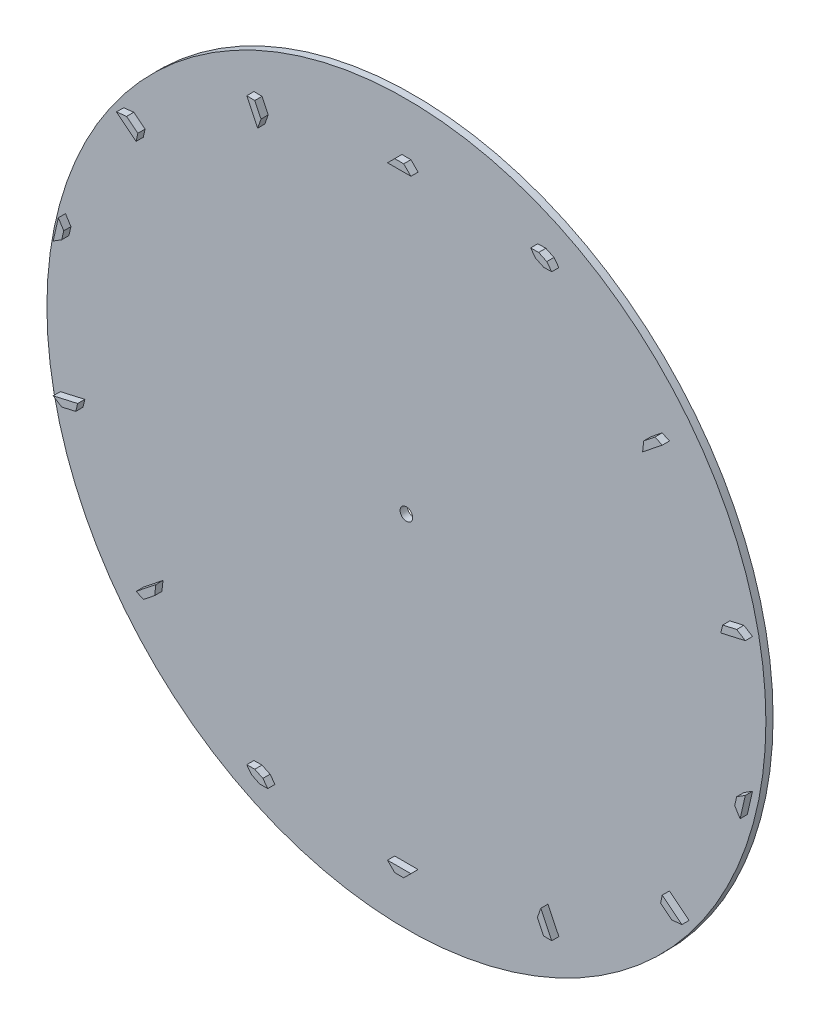
SolidWorks part; units mm, degrees
ref_plane "Front Plane" through (0, 0, 0) normal (0, 0, 1) x (1, 0, 0)
ref_plane "Top Plane" through (0, 0, 0) normal (0, 1, 0) x (1, 0, 0)
ref_plane "Right Plane" through (0, 0, 0) normal (1, 0, 0) x (0, 0, -1)
sketch "Sketch1" plane through (0, 0, 0) normal (0, 0, 1) x (1, 0, 0)
  circle A0 centre (0, 0) radius 100
  circle A1 centre (0, 0) radius 1.75
  dimension "D1" = 200
  dimension "D2" = 3.5
extrude "Boss-Extrude1" add sketch "Sketch1" along normal blind 2
sketch "Sketch2" plane through (0, 0, 2) normal (0, 0, 1) x (1, 0, 0)
  line L0 (0, 0) -> (0, -100) construction
  line L1 (0, 0) -> (-8.9639, -99.5974) construction
  line L2 (0, 0) -> (-17.8557, -98.393) construction
  line L3 (0, 0) -> (-26.6037, -96.3963) construction
  line L4 (0, 0) -> (-35.1375, -93.6235) construction
  line L5 (0, 0) -> (-43.3884, -90.0969) construction
  line L6 (0, 0) -> (-51.2899, -85.8449) construction
  line L7 (0, 0) -> (-58.7785, -80.9017) construction
  line L8 (0, 0) -> (-65.7939, -75.3071) construction
  line L9 (0, 0) -> (-72.2795, -69.1063) construction
  line L10 (0, 0) -> (-78.1831, -62.349) construction
  line L11 (0, 0) -> (-83.4573, -55.0897) construction
  line L12 (0, 0) -> (-88.0596, -47.3869) construction
  line L13 (0, 0) -> (-91.9528, -39.3025) construction
  line L14 (0, 0) -> (-95.1057, -30.9017) construction
  line L15 (0, 0) -> (-97.4928, -22.2521) construction
  line L16 (0, 0) -> (-99.095, -13.4233) construction
  line L17 (0, 0) -> (-99.8993, -4.4865) construction
  line L18 (0, 0) -> (-99.8993, 4.4865) construction
  line L19 (0, 0) -> (-99.095, 13.4233) construction
  line L20 (0, 0) -> (-97.4928, 22.2521) construction
  line L21 (0, 0) -> (-95.1057, 30.9017) construction
  line L22 (0, 0) -> (-91.9528, 39.3025) construction
  line L23 (0, 0) -> (-88.0596, 47.3869) construction
  line L24 (0, 0) -> (-83.4573, 55.0897) construction
  line L25 (0, 0) -> (-78.1831, 62.349) construction
  line L26 (0, 0) -> (-72.2795, 69.1063) construction
  line L27 (0, 0) -> (-65.7939, 75.3071) construction
  line L28 (0, 0) -> (-58.7785, 80.9017) construction
  line L29 (0, 0) -> (-51.2899, 85.8449) construction
  line L30 (0, 0) -> (-43.3884, 90.0969) construction
  line L31 (0, 0) -> (-35.1375, 93.6235) construction
  line L32 (0, 0) -> (-26.6037, 96.3963) construction
  line L33 (0, 0) -> (-17.8557, 98.393) construction
  line L34 (0, 0) -> (-8.9639, 99.5974) construction
  line L35 (0, 0) -> (0, 100) construction
  line L36 (0, 0) -> (8.9639, 99.5974) construction
  line L37 (0, 0) -> (17.8557, 98.393) construction
  line L38 (0, 0) -> (26.6037, 96.3963) construction
  line L39 (0, 0) -> (35.1375, 93.6235) construction
  line L40 (0, 0) -> (43.3884, 90.0969) construction
  line L41 (0, 0) -> (51.2899, 85.8449) construction
  line L42 (0, 0) -> (58.7785, 80.9017) construction
  line L43 (0, 0) -> (65.7939, 75.3071) construction
  line L44 (0, 0) -> (72.2795, 69.1063) construction
  line L45 (0, 0) -> (78.1831, 62.349) construction
  line L46 (0, 0) -> (83.4573, 55.0897) construction
  line L47 (0, 0) -> (88.0596, 47.3869) construction
  line L48 (0, 0) -> (91.9528, 39.3025) construction
  line L49 (0, 0) -> (95.1057, 30.9017) construction
  line L50 (0, 0) -> (97.4928, 22.2521) construction
  line L51 (0, 0) -> (99.095, 13.4233) construction
  line L52 (0, 0) -> (99.8993, 4.4865) construction
  line L53 (0, 0) -> (99.8993, -4.4865) construction
  line L54 (0, 0) -> (99.095, -13.4233) construction
  line L55 (0, 0) -> (97.4928, -22.2521) construction
  line L56 (0, 0) -> (95.1057, -30.9017) construction
  line L57 (0, 0) -> (91.9528, -39.3025) construction
  line L58 (0, 0) -> (88.0596, -47.3869) construction
  line L59 (0, 0) -> (83.4573, -55.0897) construction
  line L60 (0, 0) -> (78.1831, -62.349) construction
  line L61 (0, 0) -> (72.2795, -69.1063) construction
  line L62 (0, 0) -> (65.7939, -75.3071) construction
  line L63 (0, 0) -> (58.7785, -80.9017) construction
  line L64 (0, 0) -> (51.2899, -85.8449) construction
  line L65 (0, 0) -> (43.3884, -90.0969) construction
  line L66 (0, 0) -> (35.1375, -93.6235) construction
  line L67 (0, 0) -> (26.6037, -96.3963) construction
  line L68 (0, 0) -> (17.8557, -98.393) construction
  line L69 (0, 0) -> (8.9639, -99.5974) construction
  line L70 (-1.25, -86) -> (-3.25, -84)
  line L71 (-3.25, -98) -> (3.25, -98)
  line L72 (-3.25, -98) -> (-3.25, -84)
  line L73 (-3.25, -84) -> (3.25, -84)
  line L74 (3.25, -98) -> (3.25, -84)
  line L75 (-1.25, -96) -> (1.25, -96)
  line L76 (-1.25, -96) -> (-1.25, -86)
  line L77 (-1.25, -86) -> (1.25, -86)
  line L78 (1.25, -96) -> (1.25, -86)
  line L79 (-1.25, -90) -> (1.25, -90)
  line L80 (-1.25, -90) -> (-1.25, -92)
  line L81 (-1.25, -92) -> (1.25, -92)
  line L82 (1.25, -90) -> (1.25, -92)
  line L83 (1.25, -86) -> (3.25, -84)
  line L84 (1.25, -96) -> (3.25, -98)
  line L85 (-1.25, -96) -> (-3.25, -98)
  line L86 (-1.25, -90) -> (-3.25, -91)
  line L87 (-3.25, -91) -> (-1.25, -92)
  line L88 (1.25, -90) -> (3.25, -91)
  line L89 (3.25, -91) -> (1.25, -92)
  line L90 (-10.7666, -83.3705) -> (-4.2928, -83.9532)
  line L91 (-8.9539, -85.5417) -> (-10.7666, -83.3705)
  line L92 (-12.0216, -97.3142) -> (-10.7666, -83.3705)
  line L93 (-9.8503, -95.5015) -> (-12.0216, -97.3142)
  line L94 (-9.8503, -95.5015) -> (-8.9539, -85.5417)
  line L95 (-11.3941, -90.3423) -> (-9.4918, -91.5176)
  line L96 (-9.3125, -89.5256) -> (-11.3941, -90.3423)
  line L97 (-8.9539, -85.5417) -> (-6.464, -85.7658)
  line L98 (-6.464, -85.7658) -> (-4.2928, -83.9532)
  line L99 (-5.5477, -97.8968) -> (-4.2928, -83.9532)
  line L100 (-9.3125, -89.5256) -> (-6.8226, -89.7497)
  line L101 (-9.4918, -91.5176) -> (-7.0018, -91.7417)
  line L102 (-7.3604, -95.7256) -> (-6.464, -85.7658)
  line L103 (-6.8226, -89.7497) -> (-4.9203, -90.925)
  line L104 (-4.9203, -90.925) -> (-7.0018, -91.7417)
  line L105 (-7.3604, -95.7256) -> (-5.5477, -97.8968)
  line L106 (-9.8503, -95.5015) -> (-7.3604, -95.7256)
  line L107 (-12.0216, -97.3142) -> (-5.5477, -97.8968)
  line L108 (-18.1966, -82.0698) -> (-11.801, -83.2304)
  line L109 (-16.5858, -84.3947) -> (-18.1966, -82.0698)
  line L110 (-20.6963, -95.8448) -> (-18.1966, -82.0698)
  line L111 (-18.3714, -94.234) -> (-20.6963, -95.8448)
  line L112 (-18.3714, -94.234) -> (-16.5858, -84.3947)
  line L113 (-19.4464, -88.9573) -> (-17.6571, -90.2983)
  line L114 (-17.3, -88.3305) -> (-19.4464, -88.9573)
  line L115 (-16.5858, -84.3947) -> (-14.126, -84.8411)
  line L116 (-14.126, -84.8411) -> (-11.801, -83.2304)
  line L117 (-14.3008, -97.0054) -> (-11.801, -83.2304)
  line L118 (-17.3, -88.3305) -> (-14.8402, -88.7769)
  line L119 (-17.6571, -90.2983) -> (-15.1973, -90.7447)
  line L120 (-15.9115, -94.6804) -> (-14.126, -84.8411)
  line L121 (-14.8402, -88.7769) -> (-13.0509, -90.1179)
  line L122 (-13.0509, -90.1179) -> (-15.1973, -90.7447)
  line L123 (-15.9115, -94.6804) -> (-14.3008, -97.0054)
  line L124 (-18.3714, -94.234) -> (-15.9115, -94.6804)
  line L125 (-20.6963, -95.8448) -> (-14.3008, -97.0054)
  line L126 (-25.48, -80.1083) -> (-19.2142, -81.8375)
  line L127 (-24.0841, -82.5683) -> (-25.48, -80.1083)
  line L128 (-29.2045, -93.6037) -> (-25.48, -80.1083)
  line L129 (-26.7445, -92.2079) -> (-29.2045, -93.6037)
  line L130 (-26.7445, -92.2079) -> (-24.0841, -82.5683)
  line L131 (-27.3422, -86.856) -> (-25.6803, -88.352)
  line L132 (-25.1483, -86.4241) -> (-27.3422, -86.856)
  line L133 (-24.0841, -82.5683) -> (-21.6742, -83.2334)
  line L134 (-21.6742, -83.2334) -> (-19.2142, -81.8375)
  line L135 (-22.9387, -95.333) -> (-19.2142, -81.8375)
  line L136 (-25.1483, -86.4241) -> (-22.7384, -87.0892)
  line L137 (-25.6803, -88.352) -> (-23.2704, -89.0171)
  line L138 (-24.3346, -92.873) -> (-21.6742, -83.2334)
  line L139 (-22.7384, -87.0892) -> (-21.0765, -88.5852)
  line L140 (-21.0765, -88.5852) -> (-23.2704, -89.0171)
  line L141 (-24.3346, -92.873) -> (-22.9387, -95.333)
  line L142 (-26.7445, -92.2079) -> (-24.3346, -92.873)
  line L143 (-29.2045, -93.6037) -> (-22.9387, -95.333)
  line L144 (-32.5582, -77.5018) -> (-26.4727, -79.7857)
  line L145 (-31.3885, -80.077) -> (-32.5582, -77.5018)
  line L146 (-37.4775, -90.609) -> (-32.5582, -77.5018)
  line L147 (-34.9023, -89.4393) -> (-37.4775, -90.609)
  line L148 (-34.9023, -89.4393) -> (-31.3885, -80.077)
  line L149 (-35.0179, -84.0554) -> (-33.4968, -85.6944)
  line L150 (-32.794, -83.8219) -> (-35.0179, -84.0554)
  line L151 (-31.3885, -80.077) -> (-29.0479, -80.9554)
  line L152 (-29.0479, -80.9554) -> (-26.4727, -79.7857)
  line L153 (-31.392, -92.893) -> (-26.4727, -79.7857)
  line L154 (-32.794, -83.8219) -> (-30.4534, -84.7004)
  line L155 (-33.4968, -85.6944) -> (-31.1562, -86.5728)
  line L156 (-32.5617, -90.3178) -> (-29.0479, -80.9554)
  line L157 (-30.4534, -84.7004) -> (-28.9323, -86.3393)
  line L158 (-28.9323, -86.3393) -> (-31.1562, -86.5728)
  line L159 (-32.5617, -90.3178) -> (-31.392, -92.893)
  line L160 (-34.9023, -89.4393) -> (-32.5617, -90.3178)
  line L161 (-37.4775, -90.609) -> (-31.392, -92.893)
  line L162 (-39.3744, -74.2713) -> (-33.5181, -77.0915)
  line L163 (-38.4402, -76.941) -> (-39.3744, -74.2713)
  line L164 (-45.4488, -86.8848) -> (-39.3744, -74.2713)
  line L165 (-42.7791, -85.9507) -> (-45.4488, -86.8848)
  line L166 (-42.7791, -85.9507) -> (-38.4402, -76.941)
  line L167 (-42.4116, -80.578) -> (-41.0435, -82.3468)
  line L168 (-40.1757, -80.5448) -> (-42.4116, -80.578)
  line L169 (-38.4402, -76.941) -> (-36.1878, -78.0257)
  line L170 (-36.1878, -78.0257) -> (-33.5181, -77.0915)
  line L171 (-39.5925, -89.7051) -> (-33.5181, -77.0915)
  line L172 (-40.1757, -80.5448) -> (-37.9233, -81.6296)
  line L173 (-41.0435, -82.3468) -> (-38.7911, -83.4315)
  line L174 (-40.5266, -87.0354) -> (-36.1878, -78.0257)
  line L175 (-37.9233, -81.6296) -> (-36.5553, -83.3983)
  line L176 (-36.5553, -83.3983) -> (-38.7911, -83.4315)
  line L177 (-40.5266, -87.0354) -> (-39.5925, -89.7051)
  line L178 (-42.7791, -85.9507) -> (-40.5266, -87.0354)
  line L179 (-45.4488, -86.8848) -> (-39.5925, -89.7051)
  line L180 (-45.8735, -70.4428) -> (-40.2936, -73.7766)
  line L181 (-45.1824, -73.1855) -> (-45.8735, -70.4428)
  line L182 (-53.0541, -82.4611) -> (-45.8735, -70.4428)
  line L183 (-50.3114, -81.77) -> (-53.0541, -82.4611)
  line L184 (-50.3114, -81.77) -> (-45.1824, -73.1855)
  line L185 (-49.4638, -76.4519) -> (-48.2598, -78.3362)
  line L186 (-47.234, -76.6193) -> (-49.4638, -76.4519)
  line L187 (-45.1824, -73.1855) -> (-43.0363, -74.4677)
  line L188 (-43.0363, -74.4677) -> (-40.2936, -73.7766)
  line L189 (-47.4742, -85.7949) -> (-40.2936, -73.7766)
  line L190 (-47.234, -76.6193) -> (-45.0879, -77.9015)
  line L191 (-48.2598, -78.3362) -> (-46.1137, -79.6184)
  line L192 (-48.1653, -83.0522) -> (-43.0363, -74.4677)
  line L193 (-45.0879, -77.9015) -> (-43.8839, -79.7858)
  line L194 (-43.8839, -79.7858) -> (-46.1137, -79.6184)
  line L195 (-48.1653, -83.0522) -> (-47.4742, -85.7949)
  line L196 (-50.3114, -81.77) -> (-48.1653, -83.0522)
  line L197 (-53.0541, -82.4611) -> (-47.4742, -85.7949)
  line L198 (-52.0033, -66.0471) -> (-46.7447, -69.8677)
  line L199 (-51.5608, -68.8407) -> (-52.0033, -66.0471)
  line L200 (-60.2323, -77.3734) -> (-52.0033, -66.0471)
  line L201 (-57.4387, -76.9309) -> (-60.2323, -77.3734)
  line L202 (-57.4387, -76.9309) -> (-51.5608, -68.8407)
  line L203 (-56.1178, -71.7102) -> (-55.0875, -73.6948)
  line L204 (-53.9119, -72.0768) -> (-56.1178, -71.7102)
  line L205 (-51.5608, -68.8407) -> (-49.5383, -70.3102)
  line L206 (-49.5383, -70.3102) -> (-46.7447, -69.8677)
  line L207 (-54.9736, -81.194) -> (-46.7447, -69.8677)
  line L208 (-53.9119, -72.0768) -> (-51.8894, -73.5463)
  line L209 (-55.0875, -73.6948) -> (-53.065, -75.1643)
  line L210 (-55.4161, -78.4004) -> (-49.5383, -70.3102)
  line L211 (-51.8894, -73.5463) -> (-50.8592, -75.5308)
  line L212 (-50.8592, -75.5308) -> (-53.065, -75.1643)
  line L213 (-55.4161, -78.4004) -> (-54.9736, -81.194)
  line L214 (-57.4387, -76.9309) -> (-55.4161, -78.4004)
  line L215 (-60.2323, -77.3734) -> (-54.9736, -81.194)
  line L216 (-57.7143, -61.1197) -> (-52.8194, -65.3963)
  line L217 (-57.5241, -63.9417) -> (-57.7143, -61.1197)
  line L218 (-66.9255, -71.6627) -> (-57.7143, -61.1197)
  line L219 (-64.1035, -71.4724) -> (-66.9255, -71.6627)
  line L220 (-64.1035, -71.4724) -> (-57.5241, -63.9417)
  line L221 (-62.3199, -66.3912) -> (-61.4717, -68.4602)
  line L222 (-60.1558, -66.954) -> (-62.3199, -66.3912)
  line L223 (-57.5241, -63.9417) -> (-55.6414, -65.5866)
  line L224 (-55.6414, -65.5866) -> (-52.8194, -65.3963)
  line L225 (-62.0305, -75.9393) -> (-52.8194, -65.3963)
  line L226 (-60.1558, -66.954) -> (-58.2731, -68.5989)
  line L227 (-61.4717, -68.4602) -> (-59.589, -70.105)
  line L228 (-62.2208, -73.1173) -> (-55.6414, -65.5866)
  line L229 (-58.2731, -68.5989) -> (-57.4249, -70.6678)
  line L230 (-57.4249, -70.6678) -> (-59.589, -70.105)
  line L231 (-62.2208, -73.1173) -> (-62.0305, -75.9393)
  line L232 (-64.1035, -71.4724) -> (-62.2208, -73.1173)
  line L233 (-66.9255, -71.6627) -> (-62.0305, -75.9393)
  line L234 (-62.9607, -55.7002) -> (-58.4688, -60.3983)
  line L235 (-63.0242, -58.5279) -> (-62.9607, -55.7002)
  line L236 (-73.0799, -65.3751) -> (-62.9607, -55.7002)
  line L237 (-70.2521, -65.4385) -> (-73.0799, -65.3751)
  line L238 (-70.2521, -65.4385) -> (-63.0242, -58.5279)
  line L239 (-68.0203, -60.5376) -> (-67.361, -62.6743)
  line L240 (-65.9154, -61.2921) -> (-68.0203, -60.5376)
  line L241 (-63.0242, -58.5279) -> (-61.2965, -60.3349)
  line L242 (-61.2965, -60.3349) -> (-58.4688, -60.3983)
  line L243 (-68.5879, -70.0732) -> (-58.4688, -60.3983)
  line L244 (-65.9154, -61.2921) -> (-64.1877, -63.0991)
  line L245 (-67.361, -62.6743) -> (-65.6333, -64.4813)
  line L246 (-68.5245, -67.2455) -> (-61.2965, -60.3349)
  line L247 (-64.1877, -63.0991) -> (-63.5284, -65.2358)
  line L248 (-63.5284, -65.2358) -> (-65.6333, -64.4813)
  line L249 (-68.5245, -67.2455) -> (-68.5879, -70.0732)
  line L250 (-70.2521, -65.4385) -> (-68.5245, -67.2455)
  line L251 (-73.0799, -65.3751) -> (-68.5879, -70.0732)
  line L252 (-67.7002, -49.8322) -> (-63.6475, -54.9141)
  line L253 (-68.0169, -52.6428) -> (-67.7002, -49.8322)
  line L254 (-78.6458, -58.561) -> (-67.7002, -49.8322)
  line L255 (-75.8352, -58.8777) -> (-78.6458, -58.561)
  line L256 (-75.8352, -58.8777) -> (-68.0169, -52.6428)
  line L257 (-73.173, -54.1966) -> (-72.7079, -56.3838)
  line L258 (-71.1442, -55.1368) -> (-73.173, -54.1966)
  line L259 (-68.0169, -52.6428) -> (-66.4581, -54.5974)
  line L260 (-66.4581, -54.5974) -> (-63.6475, -54.9141)
  line L261 (-74.5931, -63.643) -> (-63.6475, -54.9141)
  line L262 (-71.1442, -55.1368) -> (-69.5855, -57.0914)
  line L263 (-72.7079, -56.3838) -> (-71.1491, -58.3384)
  line L264 (-74.2765, -60.8323) -> (-66.4581, -54.5974)
  line L265 (-69.5855, -57.0914) -> (-69.1203, -59.2785)
  line L266 (-69.1203, -59.2785) -> (-71.1491, -58.3384)
  line L267 (-74.2765, -60.8323) -> (-74.5931, -63.643)
  line L268 (-75.8352, -58.8777) -> (-74.2765, -60.8323)
  line L269 (-78.6458, -58.561) -> (-74.5931, -63.643)
  line L270 (-71.8946, -43.563) -> (-68.3137, -48.9877)
  line L271 (-72.4619, -46.3339) -> (-71.8946, -43.563)
  line L272 (-83.5786, -51.2755) -> (-71.8946, -43.563)
  line L273 (-80.8077, -51.8429) -> (-83.5786, -51.2755)
  line L274 (-80.8077, -51.8429) -> (-72.4619, -46.3339)
  line L275 (-77.7366, -47.4193) -> (-77.4694, -49.6393)
  line L276 (-75.8002, -48.5375) -> (-77.7366, -47.4193)
  line L277 (-72.4619, -46.3339) -> (-71.0847, -48.4204)
  line L278 (-71.0847, -48.4204) -> (-68.3137, -48.9877)
  line L279 (-79.9978, -56.7003) -> (-68.3137, -48.9877)
  line L280 (-75.8002, -48.5375) -> (-74.423, -50.6239)
  line L281 (-77.4694, -49.6393) -> (-76.0921, -51.7257)
  line L282 (-79.4304, -53.9293) -> (-71.0847, -48.4204)
  line L283 (-74.423, -50.6239) -> (-74.1558, -52.844)
  line L284 (-74.1558, -52.844) -> (-76.0921, -51.7257)
  line L285 (-79.4304, -53.9293) -> (-79.9978, -56.7003)
  line L286 (-80.8077, -51.8429) -> (-79.4304, -53.9293)
  line L287 (-83.5786, -51.2755) -> (-79.9978, -56.7003)
  line L288 (-75.5101, -36.943) -> (-72.43, -42.6669)
  line L289 (-76.3236, -39.652) -> (-75.5101, -36.943)
  line L290 (-87.8384, -43.5772) -> (-75.5101, -36.943)
  line L291 (-85.1295, -44.3906) -> (-87.8384, -43.5772)
  line L292 (-85.1295, -44.3906) -> (-76.3236, -39.652)
  line L293 (-81.6743, -40.2601) -> (-81.6071, -42.4952)
  line L294 (-79.8459, -41.5474) -> (-81.6743, -40.2601)
  line L295 (-76.3236, -39.652) -> (-75.1389, -41.8534)
  line L296 (-75.1389, -41.8534) -> (-72.43, -42.6669)
  line L297 (-84.7583, -49.3011) -> (-72.43, -42.6669)
  line L298 (-79.8459, -41.5474) -> (-78.6613, -43.7489)
  line L299 (-81.6071, -42.4952) -> (-80.4225, -44.6967)
  line L300 (-83.9448, -46.5921) -> (-75.1389, -41.8534)
  line L301 (-78.6613, -43.7489) -> (-78.5941, -45.984)
  line L302 (-78.5941, -45.984) -> (-80.4225, -44.6967)
  line L303 (-83.9448, -46.5921) -> (-84.7583, -49.3011)
  line L304 (-85.1295, -44.3906) -> (-83.9448, -46.5921)
  line L305 (-87.8384, -43.5772) -> (-84.7583, -49.3011)
  line L306 (-78.5177, -30.0256) -> (-75.963, -36.0026)
  line L307 (-79.5707, -32.6507) -> (-78.5177, -30.0256)
  line L308 (-91.3911, -35.528) -> (-78.5177, -30.0256)
  line L309 (-88.7659, -36.581) -> (-91.3911, -35.528)
  line L310 (-88.7659, -36.581) -> (-79.5707, -32.6507)
  line L311 (-84.9544, -32.7768) -> (-85.0878, -35.0089)
  line L312 (-83.2488, -34.2228) -> (-84.9544, -32.7768)
  line L313 (-79.5707, -32.6507) -> (-78.5881, -34.9496)
  line L314 (-78.5881, -34.9496) -> (-75.963, -36.0026)
  line L315 (-88.8364, -41.5049) -> (-75.963, -36.0026)
  line L316 (-83.2488, -34.2228) -> (-82.2662, -36.5217)
  line L317 (-85.0878, -35.0089) -> (-84.1053, -37.3077)
  line L318 (-87.7834, -38.8798) -> (-78.5881, -34.9496)
  line L319 (-82.2662, -36.5217) -> (-82.3997, -38.7537)
  line L320 (-82.3997, -38.7537) -> (-84.1053, -37.3077)
  line L321 (-87.7834, -38.8798) -> (-88.8364, -41.5049)
  line L322 (-88.7659, -36.581) -> (-87.7834, -38.8798)
  line L323 (-91.3911, -35.528) -> (-88.8364, -41.5049)
  line L324 (-80.8931, -22.8665) -> (-78.8844, -29.0484)
  line L325 (-82.1771, -25.3866) -> (-80.8931, -22.8665)
  line L326 (-94.2078, -27.1927) -> (-80.8931, -22.8665)
  line L327 (-91.6877, -28.4768) -> (-94.2078, -27.1927)
  line L328 (-91.6877, -28.4768) -> (-82.1771, -25.3866)
  line L329 (-87.5504, -25.0296) -> (-87.8835, -27.2407)
  line L330 (-85.9814, -26.6227) -> (-87.5504, -25.0296)
  line L331 (-82.1771, -25.3866) -> (-81.4046, -27.7643)
  line L332 (-81.4046, -27.7643) -> (-78.8844, -29.0484)
  line L333 (-92.1992, -33.3746) -> (-78.8844, -29.0484)
  line L334 (-85.9814, -26.6227) -> (-85.2088, -29.0004)
  line L335 (-87.8835, -27.2407) -> (-87.1109, -29.6184)
  line L336 (-90.9152, -30.8545) -> (-81.4046, -27.7643)
  line L337 (-85.2088, -29.0004) -> (-85.5418, -31.2115)
  line L338 (-85.5418, -31.2115) -> (-87.1109, -29.6184)
  line L339 (-90.9152, -30.8545) -> (-92.1992, -33.3746)
  line L340 (-91.6877, -28.4768) -> (-90.9152, -30.8545)
  line L341 (-94.2078, -27.1927) -> (-92.1992, -33.3746)
  line L342 (-82.6171, -15.5232) -> (-81.1708, -21.8603)
  line L343 (-84.122, -17.9181) -> (-82.6171, -15.5232)
  line L344 (-96.2661, -18.6385) -> (-82.6171, -15.5232)
  line L345 (-93.8712, -20.1433) -> (-96.2661, -18.6385)
  line L346 (-93.8712, -20.1433) -> (-84.122, -17.9181)
  line L347 (-89.4416, -17.0809) -> (-89.9715, -19.2533)
  line L348 (-88.0217, -18.8082) -> (-89.4416, -17.0809)
  line L349 (-84.122, -17.9181) -> (-83.5656, -20.3555)
  line L350 (-83.5656, -20.3555) -> (-81.1708, -21.8603)
  line L351 (-94.8197, -24.9756) -> (-81.1708, -21.8603)
  line L352 (-88.0217, -18.8082) -> (-87.4654, -21.2455)
  line L353 (-89.9715, -19.2533) -> (-89.4152, -21.6906)
  line L354 (-93.3149, -22.5807) -> (-83.5656, -20.3555)
  line L355 (-87.4654, -21.2455) -> (-87.9952, -23.4179)
  line L356 (-87.9952, -23.4179) -> (-89.4152, -21.6906)
  line L357 (-93.3149, -22.5807) -> (-94.8197, -24.9756)
  line L358 (-93.8712, -20.1433) -> (-93.3149, -22.5807)
  line L359 (-96.2661, -18.6385) -> (-94.8197, -24.9756)
  line L360 (-83.676, -8.055) -> (-82.8035, -14.4962)
  line L361 (-85.3895, -10.3054) -> (-83.676, -8.055)
  line L362 (-97.5493, -9.9343) -> (-83.676, -8.055)
  line L363 (-95.299, -11.6477) -> (-97.5493, -9.9343)
  line L364 (-95.299, -11.6477) -> (-85.3895, -10.3054)
  line L365 (-90.6127, -8.9946) -> (-91.3352, -11.1108)
  line L366 (-89.3533, -10.8423) -> (-90.6127, -8.9946)
  line L367 (-85.3895, -10.3054) -> (-85.0539, -12.7827)
  line L368 (-85.0539, -12.7827) -> (-82.8035, -14.4962)
  line L369 (-96.6768, -16.3754) -> (-82.8035, -14.4962)
  line L370 (-89.3533, -10.8423) -> (-89.0177, -13.3197)
  line L371 (-91.3352, -11.1108) -> (-90.9996, -13.5881)
  line L372 (-94.9634, -14.1251) -> (-85.0539, -12.7827)
  line L373 (-89.0177, -13.3197) -> (-89.7402, -15.4358)
  line L374 (-89.7402, -15.4358) -> (-90.9996, -13.5881)
  line L375 (-94.9634, -14.1251) -> (-96.6768, -16.3754)
  line L376 (-95.299, -11.6477) -> (-94.9634, -14.1251)
  line L377 (-97.5493, -9.9343) -> (-96.6768, -16.3754)
  line L378 (-84.0612, -0.5219) -> (-83.7696, -7.0154)
  line L379 (-85.9695, -2.6096) -> (-84.0612, -0.5219)
  line L380 (-98.0471, -1.15) -> (-84.0612, -0.5219)
  line L381 (-95.9594, -3.0583) -> (-98.0471, -1.15)
  line L382 (-95.9594, -3.0583) -> (-85.9695, -2.6096)
  line L383 (-91.0542, -0.836) -> (-91.9634, -2.8788)
  line L384 (-89.9655, -2.7891) -> (-91.0542, -0.836)
  line L385 (-85.9695, -2.6096) -> (-85.8573, -5.1071)
  line L386 (-85.8573, -5.1071) -> (-83.7696, -7.0154)
  line L387 (-97.7555, -7.6435) -> (-83.7696, -7.0154)
  line L388 (-89.9655, -2.7891) -> (-89.8533, -5.2866)
  line L389 (-91.9634, -2.8788) -> (-91.8513, -5.3763)
  line L390 (-95.8473, -5.5558) -> (-85.8573, -5.1071)
  line L391 (-89.8533, -5.2866) -> (-90.7626, -7.3294)
  line L392 (-90.7626, -7.3294) -> (-91.8513, -5.3763)
  line L393 (-95.8473, -5.5558) -> (-97.7555, -7.6435)
  line L394 (-95.9594, -3.0583) -> (-95.8473, -5.5558)
  line L395 (-98.0471, -1.15) -> (-97.7555, -7.6435)
  line L396 (-83.7696, 7.0154) -> (-84.0612, 0.5219)
  line L397 (-85.8573, 5.1071) -> (-83.7696, 7.0154)
  line L398 (-97.7555, 7.6435) -> (-83.7696, 7.0154)
  line L399 (-95.8473, 5.5558) -> (-97.7555, 7.6435)
  line L400 (-95.8473, 5.5558) -> (-85.8573, 5.1071)
  line L401 (-90.7626, 7.3294) -> (-91.8513, 5.3763)
  line L402 (-89.8533, 5.2866) -> (-90.7626, 7.3294)
  line L403 (-85.8573, 5.1071) -> (-85.9695, 2.6096)
  line L404 (-85.9695, 2.6096) -> (-84.0612, 0.5219)
  line L405 (-98.0471, 1.15) -> (-84.0612, 0.5219)
  line L406 (-89.8533, 5.2866) -> (-89.9655, 2.7891)
  line L407 (-91.8513, 5.3763) -> (-91.9634, 2.8788)
  line L408 (-95.9594, 3.0583) -> (-85.9695, 2.6096)
  line L409 (-89.9655, 2.7891) -> (-91.0542, 0.836)
  line L410 (-91.0542, 0.836) -> (-91.9634, 2.8788)
  line L411 (-95.9594, 3.0583) -> (-98.0471, 1.15)
  line L412 (-95.8473, 5.5558) -> (-95.9594, 3.0583)
  line L413 (-97.7555, 7.6435) -> (-98.0471, 1.15)
  line L414 (-82.8035, 14.4962) -> (-83.676, 8.055)
  line L415 (-85.0539, 12.7827) -> (-82.8035, 14.4962)
  line L416 (-96.6768, 16.3754) -> (-82.8035, 14.4962)
  line L417 (-94.9634, 14.1251) -> (-96.6768, 16.3754)
  line L418 (-94.9634, 14.1251) -> (-85.0539, 12.7827)
  line L419 (-89.7402, 15.4358) -> (-90.9996, 13.5881)
  line L420 (-89.0177, 13.3197) -> (-89.7402, 15.4358)
  line L421 (-85.0539, 12.7827) -> (-85.3895, 10.3054)
  line L422 (-85.3895, 10.3054) -> (-83.676, 8.055)
  line L423 (-97.5493, 9.9343) -> (-83.676, 8.055)
  line L424 (-89.0177, 13.3197) -> (-89.3533, 10.8423)
  line L425 (-90.9996, 13.5881) -> (-91.3352, 11.1108)
  line L426 (-95.299, 11.6477) -> (-85.3895, 10.3054)
  line L427 (-89.3533, 10.8423) -> (-90.6127, 8.9946)
  line L428 (-90.6127, 8.9946) -> (-91.3352, 11.1108)
  line L429 (-95.299, 11.6477) -> (-97.5493, 9.9343)
  line L430 (-94.9634, 14.1251) -> (-95.299, 11.6477)
  line L431 (-96.6768, 16.3754) -> (-97.5493, 9.9343)
  line L432 (-81.1708, 21.8603) -> (-82.6171, 15.5232)
  line L433 (-83.5656, 20.3555) -> (-81.1708, 21.8603)
  line L434 (-94.8197, 24.9756) -> (-81.1708, 21.8603)
  line L435 (-93.3149, 22.5807) -> (-94.8197, 24.9756)
  line L436 (-93.3149, 22.5807) -> (-83.5656, 20.3555)
  line L437 (-87.9952, 23.4179) -> (-89.4152, 21.6906)
  line L438 (-87.4654, 21.2455) -> (-87.9952, 23.4179)
  line L439 (-83.5656, 20.3555) -> (-84.122, 17.9181)
  line L440 (-84.122, 17.9181) -> (-82.6171, 15.5232)
  line L441 (-96.2661, 18.6385) -> (-82.6171, 15.5232)
  line L442 (-87.4654, 21.2455) -> (-88.0217, 18.8082)
  line L443 (-89.4152, 21.6906) -> (-89.9715, 19.2533)
  line L444 (-93.8712, 20.1433) -> (-84.122, 17.9181)
  line L445 (-88.0217, 18.8082) -> (-89.4416, 17.0809)
  line L446 (-89.4416, 17.0809) -> (-89.9715, 19.2533)
  line L447 (-93.8712, 20.1433) -> (-96.2661, 18.6385)
  line L448 (-93.3149, 22.5807) -> (-93.8712, 20.1433)
  line L449 (-94.8197, 24.9756) -> (-96.2661, 18.6385)
  line L450 (-78.8844, 29.0484) -> (-80.8931, 22.8665)
  line L451 (-81.4046, 27.7643) -> (-78.8844, 29.0484)
  line L452 (-92.1992, 33.3746) -> (-78.8844, 29.0484)
  line L453 (-90.9152, 30.8545) -> (-92.1992, 33.3746)
  line L454 (-90.9152, 30.8545) -> (-81.4046, 27.7643)
  line L455 (-85.5418, 31.2115) -> (-87.1109, 29.6184)
  line L456 (-85.2088, 29.0004) -> (-85.5418, 31.2115)
  line L457 (-81.4046, 27.7643) -> (-82.1771, 25.3866)
  line L458 (-82.1771, 25.3866) -> (-80.8931, 22.8665)
  line L459 (-94.2078, 27.1927) -> (-80.8931, 22.8665)
  line L460 (-85.2088, 29.0004) -> (-85.9814, 26.6227)
  line L461 (-87.1109, 29.6184) -> (-87.8835, 27.2407)
  line L462 (-91.6877, 28.4768) -> (-82.1771, 25.3866)
  line L463 (-85.9814, 26.6227) -> (-87.5504, 25.0296)
  line L464 (-87.5504, 25.0296) -> (-87.8835, 27.2407)
  line L465 (-91.6877, 28.4768) -> (-94.2078, 27.1927)
  line L466 (-90.9152, 30.8545) -> (-91.6877, 28.4768)
  line L467 (-92.1992, 33.3746) -> (-94.2078, 27.1927)
  line L468 (-75.963, 36.0026) -> (-78.5177, 30.0256)
  line L469 (-78.5881, 34.9496) -> (-75.963, 36.0026)
  line L470 (-88.8364, 41.5049) -> (-75.963, 36.0026)
  line L471 (-87.7834, 38.8798) -> (-88.8364, 41.5049)
  line L472 (-87.7834, 38.8798) -> (-78.5881, 34.9496)
  line L473 (-82.3997, 38.7537) -> (-84.1053, 37.3077)
  line L474 (-82.2662, 36.5217) -> (-82.3997, 38.7537)
  line L475 (-78.5881, 34.9496) -> (-79.5707, 32.6507)
  line L476 (-79.5707, 32.6507) -> (-78.5177, 30.0256)
  line L477 (-91.3911, 35.528) -> (-78.5177, 30.0256)
  line L478 (-82.2662, 36.5217) -> (-83.2488, 34.2228)
  line L479 (-84.1053, 37.3077) -> (-85.0878, 35.0089)
  line L480 (-88.7659, 36.581) -> (-79.5707, 32.6507)
  line L481 (-83.2488, 34.2228) -> (-84.9544, 32.7768)
  line L482 (-84.9544, 32.7768) -> (-85.0878, 35.0089)
  line L483 (-88.7659, 36.581) -> (-91.3911, 35.528)
  line L484 (-87.7834, 38.8798) -> (-88.7659, 36.581)
  line L485 (-88.8364, 41.5049) -> (-91.3911, 35.528)
  line L486 (-72.43, 42.6669) -> (-75.5101, 36.943)
  line L487 (-75.1389, 41.8534) -> (-72.43, 42.6669)
  line L488 (-84.7583, 49.3011) -> (-72.43, 42.6669)
  line L489 (-83.9448, 46.5921) -> (-84.7583, 49.3011)
  line L490 (-83.9448, 46.5921) -> (-75.1389, 41.8534)
  line L491 (-78.5941, 45.984) -> (-80.4225, 44.6967)
  line L492 (-78.6613, 43.7489) -> (-78.5941, 45.984)
  line L493 (-75.1389, 41.8534) -> (-76.3236, 39.652)
  line L494 (-76.3236, 39.652) -> (-75.5101, 36.943)
  line L495 (-87.8384, 43.5772) -> (-75.5101, 36.943)
  line L496 (-78.6613, 43.7489) -> (-79.8459, 41.5474)
  line L497 (-80.4225, 44.6967) -> (-81.6071, 42.4952)
  line L498 (-85.1295, 44.3906) -> (-76.3236, 39.652)
  line L499 (-79.8459, 41.5474) -> (-81.6743, 40.2601)
  line L500 (-81.6743, 40.2601) -> (-81.6071, 42.4952)
  line L501 (-85.1295, 44.3906) -> (-87.8384, 43.5772)
  line L502 (-83.9448, 46.5921) -> (-85.1295, 44.3906)
  line L503 (-84.7583, 49.3011) -> (-87.8384, 43.5772)
  line L504 (-68.3137, 48.9877) -> (-71.8946, 43.563)
  line L505 (-71.0847, 48.4204) -> (-68.3137, 48.9877)
  line L506 (-79.9978, 56.7003) -> (-68.3137, 48.9877)
  line L507 (-79.4304, 53.9293) -> (-79.9978, 56.7003)
  line L508 (-79.4304, 53.9293) -> (-71.0847, 48.4204)
  line L509 (-74.1558, 52.844) -> (-76.0921, 51.7257)
  line L510 (-74.423, 50.6239) -> (-74.1558, 52.844)
  line L511 (-71.0847, 48.4204) -> (-72.4619, 46.3339)
  line L512 (-72.4619, 46.3339) -> (-71.8946, 43.563)
  line L513 (-83.5786, 51.2755) -> (-71.8946, 43.563)
  line L514 (-74.423, 50.6239) -> (-75.8002, 48.5375)
  line L515 (-76.0921, 51.7257) -> (-77.4694, 49.6393)
  line L516 (-80.8077, 51.8429) -> (-72.4619, 46.3339)
  line L517 (-75.8002, 48.5375) -> (-77.7366, 47.4193)
  line L518 (-77.7366, 47.4193) -> (-77.4694, 49.6393)
  line L519 (-80.8077, 51.8429) -> (-83.5786, 51.2755)
  line L520 (-79.4304, 53.9293) -> (-80.8077, 51.8429)
  line L521 (-79.9978, 56.7003) -> (-83.5786, 51.2755)
  line L522 (-63.6475, 54.9141) -> (-67.7002, 49.8322)
  line L523 (-66.4581, 54.5974) -> (-63.6475, 54.9141)
  line L524 (-74.5931, 63.643) -> (-63.6475, 54.9141)
  line L525 (-74.2765, 60.8323) -> (-74.5931, 63.643)
  line L526 (-74.2765, 60.8323) -> (-66.4581, 54.5974)
  line L527 (-69.1203, 59.2785) -> (-71.1491, 58.3384)
  line L528 (-69.5855, 57.0914) -> (-69.1203, 59.2785)
  line L529 (-66.4581, 54.5974) -> (-68.0169, 52.6428)
  line L530 (-68.0169, 52.6428) -> (-67.7002, 49.8322)
  line L531 (-78.6458, 58.561) -> (-67.7002, 49.8322)
  line L532 (-69.5855, 57.0914) -> (-71.1442, 55.1368)
  line L533 (-71.1491, 58.3384) -> (-72.7079, 56.3838)
  line L534 (-75.8352, 58.8777) -> (-68.0169, 52.6428)
  line L535 (-71.1442, 55.1368) -> (-73.173, 54.1966)
  line L536 (-73.173, 54.1966) -> (-72.7079, 56.3838)
  line L537 (-75.8352, 58.8777) -> (-78.6458, 58.561)
  line L538 (-74.2765, 60.8323) -> (-75.8352, 58.8777)
  line L539 (-74.5931, 63.643) -> (-78.6458, 58.561)
  line L540 (-58.4688, 60.3983) -> (-62.9607, 55.7002)
  line L541 (-61.2965, 60.3349) -> (-58.4688, 60.3983)
  line L542 (-68.5879, 70.0732) -> (-58.4688, 60.3983)
  line L543 (-68.5245, 67.2455) -> (-68.5879, 70.0732)
  line L544 (-68.5245, 67.2455) -> (-61.2965, 60.3349)
  line L545 (-63.5284, 65.2358) -> (-65.6333, 64.4813)
  line L546 (-64.1877, 63.0991) -> (-63.5284, 65.2358)
  line L547 (-61.2965, 60.3349) -> (-63.0242, 58.5279)
  line L548 (-63.0242, 58.5279) -> (-62.9607, 55.7002)
  line L549 (-73.0799, 65.3751) -> (-62.9607, 55.7002)
  line L550 (-64.1877, 63.0991) -> (-65.9154, 61.2921)
  line L551 (-65.6333, 64.4813) -> (-67.361, 62.6743)
  line L552 (-70.2521, 65.4385) -> (-63.0242, 58.5279)
  line L553 (-65.9154, 61.2921) -> (-68.0203, 60.5376)
  line L554 (-68.0203, 60.5376) -> (-67.361, 62.6743)
  line L555 (-70.2521, 65.4385) -> (-73.0799, 65.3751)
  line L556 (-68.5245, 67.2455) -> (-70.2521, 65.4385)
  line L557 (-68.5879, 70.0732) -> (-73.0799, 65.3751)
  line L558 (-52.8194, 65.3963) -> (-57.7143, 61.1197)
  line L559 (-55.6414, 65.5866) -> (-52.8194, 65.3963)
  line L560 (-62.0305, 75.9393) -> (-52.8194, 65.3963)
  line L561 (-62.2208, 73.1173) -> (-62.0305, 75.9393)
  line L562 (-62.2208, 73.1173) -> (-55.6414, 65.5866)
  line L563 (-57.4249, 70.6678) -> (-59.589, 70.105)
  line L564 (-58.2731, 68.5989) -> (-57.4249, 70.6678)
  line L565 (-55.6414, 65.5866) -> (-57.5241, 63.9417)
  line L566 (-57.5241, 63.9417) -> (-57.7143, 61.1197)
  line L567 (-66.9255, 71.6627) -> (-57.7143, 61.1197)
  line L568 (-58.2731, 68.5989) -> (-60.1558, 66.954)
  line L569 (-59.589, 70.105) -> (-61.4717, 68.4602)
  line L570 (-64.1035, 71.4724) -> (-57.5241, 63.9417)
  line L571 (-60.1558, 66.954) -> (-62.3199, 66.3912)
  line L572 (-62.3199, 66.3912) -> (-61.4717, 68.4602)
  line L573 (-64.1035, 71.4724) -> (-66.9255, 71.6627)
  line L574 (-62.2208, 73.1173) -> (-64.1035, 71.4724)
  line L575 (-62.0305, 75.9393) -> (-66.9255, 71.6627)
  line L576 (-46.7447, 69.8677) -> (-52.0033, 66.0471)
  line L577 (-49.5383, 70.3102) -> (-46.7447, 69.8677)
  line L578 (-54.9736, 81.194) -> (-46.7447, 69.8677)
  line L579 (-55.4161, 78.4004) -> (-54.9736, 81.194)
  line L580 (-55.4161, 78.4004) -> (-49.5383, 70.3102)
  line L581 (-50.8592, 75.5308) -> (-53.065, 75.1643)
  line L582 (-51.8894, 73.5463) -> (-50.8592, 75.5308)
  line L583 (-49.5383, 70.3102) -> (-51.5608, 68.8407)
  line L584 (-51.5608, 68.8407) -> (-52.0033, 66.0471)
  line L585 (-60.2323, 77.3734) -> (-52.0033, 66.0471)
  line L586 (-51.8894, 73.5463) -> (-53.9119, 72.0768)
  line L587 (-53.065, 75.1643) -> (-55.0875, 73.6948)
  line L588 (-57.4387, 76.9309) -> (-51.5608, 68.8407)
  line L589 (-53.9119, 72.0768) -> (-56.1178, 71.7102)
  line L590 (-56.1178, 71.7102) -> (-55.0875, 73.6948)
  line L591 (-57.4387, 76.9309) -> (-60.2323, 77.3734)
  line L592 (-55.4161, 78.4004) -> (-57.4387, 76.9309)
  line L593 (-54.9736, 81.194) -> (-60.2323, 77.3734)
  line L594 (-40.2936, 73.7766) -> (-45.8735, 70.4428)
  line L595 (-43.0363, 74.4677) -> (-40.2936, 73.7766)
  line L596 (-47.4742, 85.7949) -> (-40.2936, 73.7766)
  line L597 (-48.1653, 83.0522) -> (-47.4742, 85.7949)
  line L598 (-48.1653, 83.0522) -> (-43.0363, 74.4677)
  line L599 (-43.8839, 79.7858) -> (-46.1137, 79.6184)
  line L600 (-45.0879, 77.9015) -> (-43.8839, 79.7858)
  line L601 (-43.0363, 74.4677) -> (-45.1824, 73.1855)
  line L602 (-45.1824, 73.1855) -> (-45.8735, 70.4428)
  line L603 (-53.0541, 82.4611) -> (-45.8735, 70.4428)
  line L604 (-45.0879, 77.9015) -> (-47.234, 76.6193)
  line L605 (-46.1137, 79.6184) -> (-48.2598, 78.3362)
  line L606 (-50.3114, 81.77) -> (-45.1824, 73.1855)
  line L607 (-47.234, 76.6193) -> (-49.4638, 76.4519)
  line L608 (-49.4638, 76.4519) -> (-48.2598, 78.3362)
  line L609 (-50.3114, 81.77) -> (-53.0541, 82.4611)
  line L610 (-48.1653, 83.0522) -> (-50.3114, 81.77)
  line L611 (-47.4742, 85.7949) -> (-53.0541, 82.4611)
  line L612 (-33.5181, 77.0915) -> (-39.3744, 74.2713)
  line L613 (-36.1878, 78.0257) -> (-33.5181, 77.0915)
  line L614 (-39.5925, 89.7051) -> (-33.5181, 77.0915)
  line L615 (-40.5266, 87.0354) -> (-39.5925, 89.7051)
  line L616 (-40.5266, 87.0354) -> (-36.1878, 78.0257)
  line L617 (-36.5553, 83.3983) -> (-38.7911, 83.4315)
  line L618 (-37.9233, 81.6296) -> (-36.5553, 83.3983)
  line L619 (-36.1878, 78.0257) -> (-38.4402, 76.941)
  line L620 (-38.4402, 76.941) -> (-39.3744, 74.2713)
  line L621 (-45.4488, 86.8848) -> (-39.3744, 74.2713)
  line L622 (-37.9233, 81.6296) -> (-40.1757, 80.5448)
  line L623 (-38.7911, 83.4315) -> (-41.0435, 82.3468)
  line L624 (-42.7791, 85.9507) -> (-38.4402, 76.941)
  line L625 (-40.1757, 80.5448) -> (-42.4116, 80.578)
  line L626 (-42.4116, 80.578) -> (-41.0435, 82.3468)
  line L627 (-42.7791, 85.9507) -> (-45.4488, 86.8848)
  line L628 (-40.5266, 87.0354) -> (-42.7791, 85.9507)
  line L629 (-39.5925, 89.7051) -> (-45.4488, 86.8848)
  line L630 (-26.4727, 79.7857) -> (-32.5582, 77.5018)
  line L631 (-29.0479, 80.9554) -> (-26.4727, 79.7857)
  line L632 (-31.392, 92.893) -> (-26.4727, 79.7857)
  line L633 (-32.5617, 90.3178) -> (-31.392, 92.893)
  line L634 (-32.5617, 90.3178) -> (-29.0479, 80.9554)
  line L635 (-28.9323, 86.3393) -> (-31.1562, 86.5728)
  line L636 (-30.4534, 84.7004) -> (-28.9323, 86.3393)
  line L637 (-29.0479, 80.9554) -> (-31.3885, 80.077)
  line L638 (-31.3885, 80.077) -> (-32.5582, 77.5018)
  line L639 (-37.4775, 90.609) -> (-32.5582, 77.5018)
  line L640 (-30.4534, 84.7004) -> (-32.794, 83.8219)
  line L641 (-31.1562, 86.5728) -> (-33.4968, 85.6944)
  line L642 (-34.9023, 89.4393) -> (-31.3885, 80.077)
  line L643 (-32.794, 83.8219) -> (-35.0179, 84.0554)
  line L644 (-35.0179, 84.0554) -> (-33.4968, 85.6944)
  line L645 (-34.9023, 89.4393) -> (-37.4775, 90.609)
  line L646 (-32.5617, 90.3178) -> (-34.9023, 89.4393)
  line L647 (-31.392, 92.893) -> (-37.4775, 90.609)
  line L648 (-19.2142, 81.8375) -> (-25.48, 80.1083)
  line L649 (-21.6742, 83.2334) -> (-19.2142, 81.8375)
  line L650 (-22.9387, 95.333) -> (-19.2142, 81.8375)
  line L651 (-24.3346, 92.873) -> (-22.9387, 95.333)
  line L652 (-24.3346, 92.873) -> (-21.6742, 83.2334)
  line L653 (-21.0765, 88.5852) -> (-23.2704, 89.0171)
  line L654 (-22.7384, 87.0892) -> (-21.0765, 88.5852)
  line L655 (-21.6742, 83.2334) -> (-24.0841, 82.5683)
  line L656 (-24.0841, 82.5683) -> (-25.48, 80.1083)
  line L657 (-29.2045, 93.6037) -> (-25.48, 80.1083)
  line L658 (-22.7384, 87.0892) -> (-25.1483, 86.4241)
  line L659 (-23.2704, 89.0171) -> (-25.6803, 88.352)
  line L660 (-26.7445, 92.2079) -> (-24.0841, 82.5683)
  line L661 (-25.1483, 86.4241) -> (-27.3422, 86.856)
  line L662 (-27.3422, 86.856) -> (-25.6803, 88.352)
  line L663 (-26.7445, 92.2079) -> (-29.2045, 93.6037)
  line L664 (-24.3346, 92.873) -> (-26.7445, 92.2079)
  line L665 (-22.9387, 95.333) -> (-29.2045, 93.6037)
  line L666 (-11.801, 83.2304) -> (-18.1966, 82.0698)
  line L667 (-14.126, 84.8411) -> (-11.801, 83.2304)
  line L668 (-14.3008, 97.0054) -> (-11.801, 83.2304)
  line L669 (-15.9115, 94.6804) -> (-14.3008, 97.0054)
  line L670 (-15.9115, 94.6804) -> (-14.126, 84.8411)
  line L671 (-13.0509, 90.1179) -> (-15.1973, 90.7447)
  line L672 (-14.8402, 88.7769) -> (-13.0509, 90.1179)
  line L673 (-14.126, 84.8411) -> (-16.5858, 84.3947)
  line L674 (-16.5858, 84.3947) -> (-18.1966, 82.0698)
  line L675 (-20.6963, 95.8448) -> (-18.1966, 82.0698)
  line L676 (-14.8402, 88.7769) -> (-17.3, 88.3305)
  line L677 (-15.1973, 90.7447) -> (-17.6571, 90.2983)
  line L678 (-18.3714, 94.234) -> (-16.5858, 84.3947)
  line L679 (-17.3, 88.3305) -> (-19.4464, 88.9573)
  line L680 (-19.4464, 88.9573) -> (-17.6571, 90.2983)
  line L681 (-18.3714, 94.234) -> (-20.6963, 95.8448)
  line L682 (-15.9115, 94.6804) -> (-18.3714, 94.234)
  line L683 (-14.3008, 97.0054) -> (-20.6963, 95.8448)
  line L684 (-4.2928, 83.9532) -> (-10.7666, 83.3705)
  line L685 (-6.464, 85.7658) -> (-4.2928, 83.9532)
  line L686 (-5.5477, 97.8968) -> (-4.2928, 83.9532)
  line L687 (-7.3604, 95.7256) -> (-5.5477, 97.8968)
  line L688 (-7.3604, 95.7256) -> (-6.464, 85.7658)
  line L689 (-4.9203, 90.925) -> (-7.0018, 91.7417)
  line L690 (-6.8226, 89.7497) -> (-4.9203, 90.925)
  line L691 (-6.464, 85.7658) -> (-8.9539, 85.5417)
  line L692 (-8.9539, 85.5417) -> (-10.7666, 83.3705)
  line L693 (-12.0216, 97.3142) -> (-10.7666, 83.3705)
  line L694 (-6.8226, 89.7497) -> (-9.3125, 89.5256)
  line L695 (-7.0018, 91.7417) -> (-9.4918, 91.5176)
  line L696 (-9.8503, 95.5015) -> (-8.9539, 85.5417)
  line L697 (-9.3125, 89.5256) -> (-11.3941, 90.3423)
  line L698 (-11.3941, 90.3423) -> (-9.4918, 91.5176)
  line L699 (-9.8503, 95.5015) -> (-12.0216, 97.3142)
  line L700 (-7.3604, 95.7256) -> (-9.8503, 95.5015)
  line L701 (-5.5477, 97.8968) -> (-12.0216, 97.3142)
  line L702 (3.25, 84) -> (-3.25, 84)
  line L703 (1.25, 86) -> (3.25, 84)
  line L704 (3.25, 98) -> (3.25, 84)
  line L705 (1.25, 96) -> (3.25, 98)
  line L706 (1.25, 96) -> (1.25, 86)
  line L707 (3.25, 91) -> (1.25, 92)
  line L708 (1.25, 90) -> (3.25, 91)
  line L709 (1.25, 86) -> (-1.25, 86)
  line L710 (-1.25, 86) -> (-3.25, 84)
  line L711 (-3.25, 98) -> (-3.25, 84)
  line L712 (1.25, 90) -> (-1.25, 90)
  line L713 (1.25, 92) -> (-1.25, 92)
  line L714 (-1.25, 96) -> (-1.25, 86)
  line L715 (-1.25, 90) -> (-3.25, 91)
  line L716 (-3.25, 91) -> (-1.25, 92)
  line L717 (-1.25, 96) -> (-3.25, 98)
  line L718 (1.25, 96) -> (-1.25, 96)
  line L719 (3.25, 98) -> (-3.25, 98)
  line L720 (10.7666, 83.3705) -> (4.2928, 83.9532)
  line L721 (8.9539, 85.5417) -> (10.7666, 83.3705)
  line L722 (12.0216, 97.3142) -> (10.7666, 83.3705)
  line L723 (9.8503, 95.5015) -> (12.0216, 97.3142)
  line L724 (9.8503, 95.5015) -> (8.9539, 85.5417)
  line L725 (11.3941, 90.3423) -> (9.4918, 91.5176)
  line L726 (9.3125, 89.5256) -> (11.3941, 90.3423)
  line L727 (8.9539, 85.5417) -> (6.464, 85.7658)
  line L728 (6.464, 85.7658) -> (4.2928, 83.9532)
  line L729 (5.5477, 97.8968) -> (4.2928, 83.9532)
  line L730 (9.3125, 89.5256) -> (6.8226, 89.7497)
  line L731 (9.4918, 91.5176) -> (7.0018, 91.7417)
  line L732 (7.3604, 95.7256) -> (6.464, 85.7658)
  line L733 (6.8226, 89.7497) -> (4.9203, 90.925)
  line L734 (4.9203, 90.925) -> (7.0018, 91.7417)
  line L735 (7.3604, 95.7256) -> (5.5477, 97.8968)
  line L736 (9.8503, 95.5015) -> (7.3604, 95.7256)
  line L737 (12.0216, 97.3142) -> (5.5477, 97.8968)
  line L738 (18.1966, 82.0698) -> (11.801, 83.2304)
  line L739 (16.5858, 84.3947) -> (18.1966, 82.0698)
  line L740 (20.6963, 95.8448) -> (18.1966, 82.0698)
  line L741 (18.3714, 94.234) -> (20.6963, 95.8448)
  line L742 (18.3714, 94.234) -> (16.5858, 84.3947)
  line L743 (19.4464, 88.9573) -> (17.6571, 90.2983)
  line L744 (17.3, 88.3305) -> (19.4464, 88.9573)
  line L745 (16.5858, 84.3947) -> (14.126, 84.8411)
  line L746 (14.126, 84.8411) -> (11.801, 83.2304)
  line L747 (14.3008, 97.0054) -> (11.801, 83.2304)
  line L748 (17.3, 88.3305) -> (14.8402, 88.7769)
  line L749 (17.6571, 90.2983) -> (15.1973, 90.7447)
  line L750 (15.9115, 94.6804) -> (14.126, 84.8411)
  line L751 (14.8402, 88.7769) -> (13.0509, 90.1179)
  line L752 (13.0509, 90.1179) -> (15.1973, 90.7447)
  line L753 (15.9115, 94.6804) -> (14.3008, 97.0054)
  line L754 (18.3714, 94.234) -> (15.9115, 94.6804)
  line L755 (20.6963, 95.8448) -> (14.3008, 97.0054)
  line L756 (25.48, 80.1083) -> (19.2142, 81.8375)
  line L757 (24.0841, 82.5683) -> (25.48, 80.1083)
  line L758 (29.2045, 93.6037) -> (25.48, 80.1083)
  line L759 (26.7445, 92.2079) -> (29.2045, 93.6037)
  line L760 (26.7445, 92.2079) -> (24.0841, 82.5683)
  line L761 (27.3422, 86.856) -> (25.6803, 88.352)
  line L762 (25.1483, 86.4241) -> (27.3422, 86.856)
  line L763 (24.0841, 82.5683) -> (21.6742, 83.2334)
  line L764 (21.6742, 83.2334) -> (19.2142, 81.8375)
  line L765 (22.9387, 95.333) -> (19.2142, 81.8375)
  line L766 (25.1483, 86.4241) -> (22.7384, 87.0892)
  line L767 (25.6803, 88.352) -> (23.2704, 89.0171)
  line L768 (24.3346, 92.873) -> (21.6742, 83.2334)
  line L769 (22.7384, 87.0892) -> (21.0765, 88.5852)
  line L770 (21.0765, 88.5852) -> (23.2704, 89.0171)
  line L771 (24.3346, 92.873) -> (22.9387, 95.333)
  line L772 (26.7445, 92.2079) -> (24.3346, 92.873)
  line L773 (29.2045, 93.6037) -> (22.9387, 95.333)
  line L774 (32.5582, 77.5018) -> (26.4727, 79.7857)
  line L775 (31.3885, 80.077) -> (32.5582, 77.5018)
  line L776 (37.4775, 90.609) -> (32.5582, 77.5018)
  line L777 (34.9023, 89.4393) -> (37.4775, 90.609)
  line L778 (34.9023, 89.4393) -> (31.3885, 80.077)
  line L779 (35.0179, 84.0554) -> (33.4968, 85.6944)
  line L780 (32.794, 83.8219) -> (35.0179, 84.0554)
  line L781 (31.3885, 80.077) -> (29.0479, 80.9554)
  line L782 (29.0479, 80.9554) -> (26.4727, 79.7857)
  line L783 (31.392, 92.893) -> (26.4727, 79.7857)
  line L784 (32.794, 83.8219) -> (30.4534, 84.7004)
  line L785 (33.4968, 85.6944) -> (31.1562, 86.5728)
  line L786 (32.5617, 90.3178) -> (29.0479, 80.9554)
  line L787 (30.4534, 84.7004) -> (28.9323, 86.3393)
  line L788 (28.9323, 86.3393) -> (31.1562, 86.5728)
  line L789 (32.5617, 90.3178) -> (31.392, 92.893)
  line L790 (34.9023, 89.4393) -> (32.5617, 90.3178)
  line L791 (37.4775, 90.609) -> (31.392, 92.893)
  line L792 (39.3744, 74.2713) -> (33.5181, 77.0915)
  line L793 (38.4402, 76.941) -> (39.3744, 74.2713)
  line L794 (45.4488, 86.8848) -> (39.3744, 74.2713)
  line L795 (42.7791, 85.9507) -> (45.4488, 86.8848)
  line L796 (42.7791, 85.9507) -> (38.4402, 76.941)
  line L797 (42.4116, 80.578) -> (41.0435, 82.3468)
  line L798 (40.1757, 80.5448) -> (42.4116, 80.578)
  line L799 (38.4402, 76.941) -> (36.1878, 78.0257)
  line L800 (36.1878, 78.0257) -> (33.5181, 77.0915)
  line L801 (39.5925, 89.7051) -> (33.5181, 77.0915)
  line L802 (40.1757, 80.5448) -> (37.9233, 81.6296)
  line L803 (41.0435, 82.3468) -> (38.7911, 83.4315)
  line L804 (40.5266, 87.0354) -> (36.1878, 78.0257)
  line L805 (37.9233, 81.6296) -> (36.5553, 83.3983)
  line L806 (36.5553, 83.3983) -> (38.7911, 83.4315)
  line L807 (40.5266, 87.0354) -> (39.5925, 89.7051)
  line L808 (42.7791, 85.9507) -> (40.5266, 87.0354)
  line L809 (45.4488, 86.8848) -> (39.5925, 89.7051)
  line L810 (45.8735, 70.4428) -> (40.2936, 73.7766)
  line L811 (45.1824, 73.1855) -> (45.8735, 70.4428)
  line L812 (53.0541, 82.4611) -> (45.8735, 70.4428)
  line L813 (50.3114, 81.77) -> (53.0541, 82.4611)
  line L814 (50.3114, 81.77) -> (45.1824, 73.1855)
  line L815 (49.4638, 76.4519) -> (48.2598, 78.3362)
  line L816 (47.234, 76.6193) -> (49.4638, 76.4519)
  line L817 (45.1824, 73.1855) -> (43.0363, 74.4677)
  line L818 (43.0363, 74.4677) -> (40.2936, 73.7766)
  line L819 (47.4742, 85.7949) -> (40.2936, 73.7766)
  line L820 (47.234, 76.6193) -> (45.0879, 77.9015)
  line L821 (48.2598, 78.3362) -> (46.1137, 79.6184)
  line L822 (48.1653, 83.0522) -> (43.0363, 74.4677)
  line L823 (45.0879, 77.9015) -> (43.8839, 79.7858)
  line L824 (43.8839, 79.7858) -> (46.1137, 79.6184)
  line L825 (48.1653, 83.0522) -> (47.4742, 85.7949)
  line L826 (50.3114, 81.77) -> (48.1653, 83.0522)
  line L827 (53.0541, 82.4611) -> (47.4742, 85.7949)
  line L828 (52.0033, 66.0471) -> (46.7447, 69.8677)
  line L829 (51.5608, 68.8407) -> (52.0033, 66.0471)
  line L830 (60.2323, 77.3734) -> (52.0033, 66.0471)
  line L831 (57.4387, 76.9309) -> (60.2323, 77.3734)
  line L832 (57.4387, 76.9309) -> (51.5608, 68.8407)
  line L833 (56.1178, 71.7102) -> (55.0875, 73.6948)
  line L834 (53.9119, 72.0768) -> (56.1178, 71.7102)
  line L835 (51.5608, 68.8407) -> (49.5383, 70.3102)
  line L836 (49.5383, 70.3102) -> (46.7447, 69.8677)
  line L837 (54.9736, 81.194) -> (46.7447, 69.8677)
  line L838 (53.9119, 72.0768) -> (51.8894, 73.5463)
  line L839 (55.0875, 73.6948) -> (53.065, 75.1643)
  line L840 (55.4161, 78.4004) -> (49.5383, 70.3102)
  line L841 (51.8894, 73.5463) -> (50.8592, 75.5308)
  line L842 (50.8592, 75.5308) -> (53.065, 75.1643)
  line L843 (55.4161, 78.4004) -> (54.9736, 81.194)
  line L844 (57.4387, 76.9309) -> (55.4161, 78.4004)
  line L845 (60.2323, 77.3734) -> (54.9736, 81.194)
  line L846 (57.7143, 61.1197) -> (52.8194, 65.3963)
  line L847 (57.5241, 63.9417) -> (57.7143, 61.1197)
  line L848 (66.9255, 71.6627) -> (57.7143, 61.1197)
  line L849 (64.1035, 71.4724) -> (66.9255, 71.6627)
  line L850 (64.1035, 71.4724) -> (57.5241, 63.9417)
  line L851 (62.3199, 66.3912) -> (61.4717, 68.4602)
  line L852 (60.1558, 66.954) -> (62.3199, 66.3912)
  line L853 (57.5241, 63.9417) -> (55.6414, 65.5866)
  line L854 (55.6414, 65.5866) -> (52.8194, 65.3963)
  line L855 (62.0305, 75.9393) -> (52.8194, 65.3963)
  line L856 (60.1558, 66.954) -> (58.2731, 68.5989)
  line L857 (61.4717, 68.4602) -> (59.589, 70.105)
  line L858 (62.2208, 73.1173) -> (55.6414, 65.5866)
  line L859 (58.2731, 68.5989) -> (57.4249, 70.6678)
  line L860 (57.4249, 70.6678) -> (59.589, 70.105)
  line L861 (62.2208, 73.1173) -> (62.0305, 75.9393)
  line L862 (64.1035, 71.4724) -> (62.2208, 73.1173)
  line L863 (66.9255, 71.6627) -> (62.0305, 75.9393)
  line L864 (62.9607, 55.7002) -> (58.4688, 60.3983)
  line L865 (63.0242, 58.5279) -> (62.9607, 55.7002)
  line L866 (73.0799, 65.3751) -> (62.9607, 55.7002)
  line L867 (70.2521, 65.4385) -> (73.0799, 65.3751)
  line L868 (70.2521, 65.4385) -> (63.0242, 58.5279)
  line L869 (68.0203, 60.5376) -> (67.361, 62.6743)
  line L870 (65.9154, 61.2921) -> (68.0203, 60.5376)
  line L871 (63.0242, 58.5279) -> (61.2965, 60.3349)
  line L872 (61.2965, 60.3349) -> (58.4688, 60.3983)
  line L873 (68.5879, 70.0732) -> (58.4688, 60.3983)
  line L874 (65.9154, 61.2921) -> (64.1877, 63.0991)
  line L875 (67.361, 62.6743) -> (65.6333, 64.4813)
  line L876 (68.5245, 67.2455) -> (61.2965, 60.3349)
  line L877 (64.1877, 63.0991) -> (63.5284, 65.2358)
  line L878 (63.5284, 65.2358) -> (65.6333, 64.4813)
  line L879 (68.5245, 67.2455) -> (68.5879, 70.0732)
  line L880 (70.2521, 65.4385) -> (68.5245, 67.2455)
  line L881 (73.0799, 65.3751) -> (68.5879, 70.0732)
  line L882 (67.7002, 49.8322) -> (63.6475, 54.9141)
  line L883 (68.0169, 52.6428) -> (67.7002, 49.8322)
  line L884 (78.6458, 58.561) -> (67.7002, 49.8322)
  line L885 (75.8352, 58.8777) -> (78.6458, 58.561)
  line L886 (75.8352, 58.8777) -> (68.0169, 52.6428)
  line L887 (73.173, 54.1966) -> (72.7079, 56.3838)
  line L888 (71.1442, 55.1368) -> (73.173, 54.1966)
  line L889 (68.0169, 52.6428) -> (66.4581, 54.5974)
  line L890 (66.4581, 54.5974) -> (63.6475, 54.9141)
  line L891 (74.5931, 63.643) -> (63.6475, 54.9141)
  line L892 (71.1442, 55.1368) -> (69.5855, 57.0914)
  line L893 (72.7079, 56.3838) -> (71.1491, 58.3384)
  line L894 (74.2765, 60.8323) -> (66.4581, 54.5974)
  line L895 (69.5855, 57.0914) -> (69.1203, 59.2785)
  line L896 (69.1203, 59.2785) -> (71.1491, 58.3384)
  line L897 (74.2765, 60.8323) -> (74.5931, 63.643)
  line L898 (75.8352, 58.8777) -> (74.2765, 60.8323)
  line L899 (78.6458, 58.561) -> (74.5931, 63.643)
  line L900 (71.8946, 43.563) -> (68.3137, 48.9877)
  line L901 (72.4619, 46.3339) -> (71.8946, 43.563)
  line L902 (83.5786, 51.2755) -> (71.8946, 43.563)
  line L903 (80.8077, 51.8429) -> (83.5786, 51.2755)
  line L904 (80.8077, 51.8429) -> (72.4619, 46.3339)
  line L905 (77.7366, 47.4193) -> (77.4694, 49.6393)
  line L906 (75.8002, 48.5375) -> (77.7366, 47.4193)
  line L907 (72.4619, 46.3339) -> (71.0847, 48.4204)
  line L908 (71.0847, 48.4204) -> (68.3137, 48.9877)
  line L909 (79.9978, 56.7003) -> (68.3137, 48.9877)
  line L910 (75.8002, 48.5375) -> (74.423, 50.6239)
  line L911 (77.4694, 49.6393) -> (76.0921, 51.7257)
  line L912 (79.4304, 53.9293) -> (71.0847, 48.4204)
  line L913 (74.423, 50.6239) -> (74.1558, 52.844)
  line L914 (74.1558, 52.844) -> (76.0921, 51.7257)
  line L915 (79.4304, 53.9293) -> (79.9978, 56.7003)
  line L916 (80.8077, 51.8429) -> (79.4304, 53.9293)
  line L917 (83.5786, 51.2755) -> (79.9978, 56.7003)
  line L918 (75.5101, 36.943) -> (72.43, 42.6669)
  line L919 (76.3236, 39.652) -> (75.5101, 36.943)
  line L920 (87.8384, 43.5772) -> (75.5101, 36.943)
  line L921 (85.1295, 44.3906) -> (87.8384, 43.5772)
  line L922 (85.1295, 44.3906) -> (76.3236, 39.652)
  line L923 (81.6743, 40.2601) -> (81.6071, 42.4952)
  line L924 (79.8459, 41.5474) -> (81.6743, 40.2601)
  line L925 (76.3236, 39.652) -> (75.1389, 41.8534)
  line L926 (75.1389, 41.8534) -> (72.43, 42.6669)
  line L927 (84.7583, 49.3011) -> (72.43, 42.6669)
  line L928 (79.8459, 41.5474) -> (78.6613, 43.7489)
  line L929 (81.6071, 42.4952) -> (80.4225, 44.6967)
  line L930 (83.9448, 46.5921) -> (75.1389, 41.8534)
  line L931 (78.6613, 43.7489) -> (78.5941, 45.984)
  line L932 (78.5941, 45.984) -> (80.4225, 44.6967)
  line L933 (83.9448, 46.5921) -> (84.7583, 49.3011)
  line L934 (85.1295, 44.3906) -> (83.9448, 46.5921)
  line L935 (87.8384, 43.5772) -> (84.7583, 49.3011)
  line L936 (78.5177, 30.0256) -> (75.963, 36.0026)
  line L937 (79.5707, 32.6507) -> (78.5177, 30.0256)
  line L938 (91.3911, 35.528) -> (78.5177, 30.0256)
  line L939 (88.7659, 36.581) -> (91.3911, 35.528)
  line L940 (88.7659, 36.581) -> (79.5707, 32.6507)
  line L941 (84.9544, 32.7768) -> (85.0878, 35.0089)
  line L942 (83.2488, 34.2228) -> (84.9544, 32.7768)
  line L943 (79.5707, 32.6507) -> (78.5881, 34.9496)
  line L944 (78.5881, 34.9496) -> (75.963, 36.0026)
  line L945 (88.8364, 41.5049) -> (75.963, 36.0026)
  line L946 (83.2488, 34.2228) -> (82.2662, 36.5217)
  line L947 (85.0878, 35.0089) -> (84.1053, 37.3077)
  line L948 (87.7834, 38.8798) -> (78.5881, 34.9496)
  line L949 (82.2662, 36.5217) -> (82.3997, 38.7537)
  line L950 (82.3997, 38.7537) -> (84.1053, 37.3077)
  line L951 (87.7834, 38.8798) -> (88.8364, 41.5049)
  line L952 (88.7659, 36.581) -> (87.7834, 38.8798)
  line L953 (91.3911, 35.528) -> (88.8364, 41.5049)
  line L954 (80.8931, 22.8665) -> (78.8844, 29.0484)
  line L955 (82.1771, 25.3866) -> (80.8931, 22.8665)
  line L956 (94.2078, 27.1927) -> (80.8931, 22.8665)
  line L957 (91.6877, 28.4768) -> (94.2078, 27.1927)
  line L958 (91.6877, 28.4768) -> (82.1771, 25.3866)
  line L959 (87.5504, 25.0296) -> (87.8835, 27.2407)
  line L960 (85.9814, 26.6227) -> (87.5504, 25.0296)
  line L961 (82.1771, 25.3866) -> (81.4046, 27.7643)
  line L962 (81.4046, 27.7643) -> (78.8844, 29.0484)
  line L963 (92.1992, 33.3746) -> (78.8844, 29.0484)
  line L964 (85.9814, 26.6227) -> (85.2088, 29.0004)
  line L965 (87.8835, 27.2407) -> (87.1109, 29.6184)
  line L966 (90.9152, 30.8545) -> (81.4046, 27.7643)
  line L967 (85.2088, 29.0004) -> (85.5418, 31.2115)
  line L968 (85.5418, 31.2115) -> (87.1109, 29.6184)
  line L969 (90.9152, 30.8545) -> (92.1992, 33.3746)
  line L970 (91.6877, 28.4768) -> (90.9152, 30.8545)
  line L971 (94.2078, 27.1927) -> (92.1992, 33.3746)
  line L972 (82.6171, 15.5232) -> (81.1708, 21.8603)
  line L973 (84.122, 17.9181) -> (82.6171, 15.5232)
  line L974 (96.2661, 18.6385) -> (82.6171, 15.5232)
  line L975 (93.8712, 20.1433) -> (96.2661, 18.6385)
  line L976 (93.8712, 20.1433) -> (84.122, 17.9181)
  line L977 (89.4416, 17.0809) -> (89.9715, 19.2533)
  line L978 (88.0217, 18.8082) -> (89.4416, 17.0809)
  line L979 (84.122, 17.9181) -> (83.5656, 20.3555)
  line L980 (83.5656, 20.3555) -> (81.1708, 21.8603)
  line L981 (94.8197, 24.9756) -> (81.1708, 21.8603)
  line L982 (88.0217, 18.8082) -> (87.4654, 21.2455)
  line L983 (89.9715, 19.2533) -> (89.4152, 21.6906)
  line L984 (93.3149, 22.5807) -> (83.5656, 20.3555)
  line L985 (87.4654, 21.2455) -> (87.9952, 23.4179)
  line L986 (87.9952, 23.4179) -> (89.4152, 21.6906)
  line L987 (93.3149, 22.5807) -> (94.8197, 24.9756)
  line L988 (93.8712, 20.1433) -> (93.3149, 22.5807)
  line L989 (96.2661, 18.6385) -> (94.8197, 24.9756)
  line L990 (83.676, 8.055) -> (82.8035, 14.4962)
  line L991 (85.3895, 10.3054) -> (83.676, 8.055)
  line L992 (97.5493, 9.9343) -> (83.676, 8.055)
  line L993 (95.299, 11.6477) -> (97.5493, 9.9343)
  line L994 (95.299, 11.6477) -> (85.3895, 10.3054)
  line L995 (90.6127, 8.9946) -> (91.3352, 11.1108)
  line L996 (89.3533, 10.8423) -> (90.6127, 8.9946)
  line L997 (85.3895, 10.3054) -> (85.0539, 12.7827)
  line L998 (85.0539, 12.7827) -> (82.8035, 14.4962)
  line L999 (96.6768, 16.3754) -> (82.8035, 14.4962)
  line L1000 (89.3533, 10.8423) -> (89.0177, 13.3197)
  line L1001 (91.3352, 11.1108) -> (90.9996, 13.5881)
  line L1002 (94.9634, 14.1251) -> (85.0539, 12.7827)
  line L1003 (89.0177, 13.3197) -> (89.7402, 15.4358)
  line L1004 (89.7402, 15.4358) -> (90.9996, 13.5881)
  line L1005 (94.9634, 14.1251) -> (96.6768, 16.3754)
  line L1006 (95.299, 11.6477) -> (94.9634, 14.1251)
  line L1007 (97.5493, 9.9343) -> (96.6768, 16.3754)
  line L1008 (84.0612, 0.5219) -> (83.7696, 7.0154)
  line L1009 (85.9695, 2.6096) -> (84.0612, 0.5219)
  line L1010 (98.0471, 1.15) -> (84.0612, 0.5219)
  line L1011 (95.9594, 3.0583) -> (98.0471, 1.15)
  line L1012 (95.9594, 3.0583) -> (85.9695, 2.6096)
  line L1013 (91.0542, 0.836) -> (91.9634, 2.8788)
  line L1014 (89.9655, 2.7891) -> (91.0542, 0.836)
  line L1015 (85.9695, 2.6096) -> (85.8573, 5.1071)
  line L1016 (85.8573, 5.1071) -> (83.7696, 7.0154)
  line L1017 (97.7555, 7.6435) -> (83.7696, 7.0154)
  line L1018 (89.9655, 2.7891) -> (89.8533, 5.2866)
  line L1019 (91.9634, 2.8788) -> (91.8513, 5.3763)
  line L1020 (95.8473, 5.5558) -> (85.8573, 5.1071)
  line L1021 (89.8533, 5.2866) -> (90.7626, 7.3294)
  line L1022 (90.7626, 7.3294) -> (91.8513, 5.3763)
  line L1023 (95.8473, 5.5558) -> (97.7555, 7.6435)
  line L1024 (95.9594, 3.0583) -> (95.8473, 5.5558)
  line L1025 (98.0471, 1.15) -> (97.7555, 7.6435)
  line L1026 (83.7696, -7.0154) -> (84.0612, -0.5219)
  line L1027 (85.8573, -5.1071) -> (83.7696, -7.0154)
  line L1028 (97.7555, -7.6435) -> (83.7696, -7.0154)
  line L1029 (95.8473, -5.5558) -> (97.7555, -7.6435)
  line L1030 (95.8473, -5.5558) -> (85.8573, -5.1071)
  line L1031 (90.7626, -7.3294) -> (91.8513, -5.3763)
  line L1032 (89.8533, -5.2866) -> (90.7626, -7.3294)
  line L1033 (85.8573, -5.1071) -> (85.9695, -2.6096)
  line L1034 (85.9695, -2.6096) -> (84.0612, -0.5219)
  line L1035 (98.0471, -1.15) -> (84.0612, -0.5219)
  line L1036 (89.8533, -5.2866) -> (89.9655, -2.7891)
  line L1037 (91.8513, -5.3763) -> (91.9634, -2.8788)
  line L1038 (95.9594, -3.0583) -> (85.9695, -2.6096)
  line L1039 (89.9655, -2.7891) -> (91.0542, -0.836)
  line L1040 (91.0542, -0.836) -> (91.9634, -2.8788)
  line L1041 (95.9594, -3.0583) -> (98.0471, -1.15)
  line L1042 (95.8473, -5.5558) -> (95.9594, -3.0583)
  line L1043 (97.7555, -7.6435) -> (98.0471, -1.15)
  line L1044 (82.8035, -14.4962) -> (83.676, -8.055)
  line L1045 (85.0539, -12.7827) -> (82.8035, -14.4962)
  line L1046 (96.6768, -16.3754) -> (82.8035, -14.4962)
  line L1047 (94.9634, -14.1251) -> (96.6768, -16.3754)
  line L1048 (94.9634, -14.1251) -> (85.0539, -12.7827)
  line L1049 (89.7402, -15.4358) -> (90.9996, -13.5881)
  line L1050 (89.0177, -13.3197) -> (89.7402, -15.4358)
  line L1051 (85.0539, -12.7827) -> (85.3895, -10.3054)
  line L1052 (85.3895, -10.3054) -> (83.676, -8.055)
  line L1053 (97.5493, -9.9343) -> (83.676, -8.055)
  line L1054 (89.0177, -13.3197) -> (89.3533, -10.8423)
  line L1055 (90.9996, -13.5881) -> (91.3352, -11.1108)
  line L1056 (95.299, -11.6477) -> (85.3895, -10.3054)
  line L1057 (89.3533, -10.8423) -> (90.6127, -8.9946)
  line L1058 (90.6127, -8.9946) -> (91.3352, -11.1108)
  line L1059 (95.299, -11.6477) -> (97.5493, -9.9343)
  line L1060 (94.9634, -14.1251) -> (95.299, -11.6477)
  line L1061 (96.6768, -16.3754) -> (97.5493, -9.9343)
  line L1062 (81.1708, -21.8603) -> (82.6171, -15.5232)
  line L1063 (83.5656, -20.3555) -> (81.1708, -21.8603)
  line L1064 (94.8197, -24.9756) -> (81.1708, -21.8603)
  line L1065 (93.3149, -22.5807) -> (94.8197, -24.9756)
  line L1066 (93.3149, -22.5807) -> (83.5656, -20.3555)
  line L1067 (87.9952, -23.4179) -> (89.4152, -21.6906)
  line L1068 (87.4654, -21.2455) -> (87.9952, -23.4179)
  line L1069 (83.5656, -20.3555) -> (84.122, -17.9181)
  line L1070 (84.122, -17.9181) -> (82.6171, -15.5232)
  line L1071 (96.2661, -18.6385) -> (82.6171, -15.5232)
  line L1072 (87.4654, -21.2455) -> (88.0217, -18.8082)
  line L1073 (89.4152, -21.6906) -> (89.9715, -19.2533)
  line L1074 (93.8712, -20.1433) -> (84.122, -17.9181)
  line L1075 (88.0217, -18.8082) -> (89.4416, -17.0809)
  line L1076 (89.4416, -17.0809) -> (89.9715, -19.2533)
  line L1077 (93.8712, -20.1433) -> (96.2661, -18.6385)
  line L1078 (93.3149, -22.5807) -> (93.8712, -20.1433)
  line L1079 (94.8197, -24.9756) -> (96.2661, -18.6385)
  line L1080 (78.8844, -29.0484) -> (80.8931, -22.8665)
  line L1081 (81.4046, -27.7643) -> (78.8844, -29.0484)
  line L1082 (92.1992, -33.3746) -> (78.8844, -29.0484)
  line L1083 (90.9152, -30.8545) -> (92.1992, -33.3746)
  line L1084 (90.9152, -30.8545) -> (81.4046, -27.7643)
  line L1085 (85.5418, -31.2115) -> (87.1109, -29.6184)
  line L1086 (85.2088, -29.0004) -> (85.5418, -31.2115)
  line L1087 (81.4046, -27.7643) -> (82.1771, -25.3866)
  line L1088 (82.1771, -25.3866) -> (80.8931, -22.8665)
  line L1089 (94.2078, -27.1927) -> (80.8931, -22.8665)
  line L1090 (85.2088, -29.0004) -> (85.9814, -26.6227)
  line L1091 (87.1109, -29.6184) -> (87.8835, -27.2407)
  line L1092 (91.6877, -28.4768) -> (82.1771, -25.3866)
  line L1093 (85.9814, -26.6227) -> (87.5504, -25.0296)
  line L1094 (87.5504, -25.0296) -> (87.8835, -27.2407)
  line L1095 (91.6877, -28.4768) -> (94.2078, -27.1927)
  line L1096 (90.9152, -30.8545) -> (91.6877, -28.4768)
  line L1097 (92.1992, -33.3746) -> (94.2078, -27.1927)
  line L1098 (75.963, -36.0026) -> (78.5177, -30.0256)
  line L1099 (78.5881, -34.9496) -> (75.963, -36.0026)
  line L1100 (88.8364, -41.5049) -> (75.963, -36.0026)
  line L1101 (87.7834, -38.8798) -> (88.8364, -41.5049)
  line L1102 (87.7834, -38.8798) -> (78.5881, -34.9496)
  line L1103 (82.3997, -38.7537) -> (84.1053, -37.3077)
  line L1104 (82.2662, -36.5217) -> (82.3997, -38.7537)
  line L1105 (78.5881, -34.9496) -> (79.5707, -32.6507)
  line L1106 (79.5707, -32.6507) -> (78.5177, -30.0256)
  line L1107 (91.3911, -35.528) -> (78.5177, -30.0256)
  line L1108 (82.2662, -36.5217) -> (83.2488, -34.2228)
  line L1109 (84.1053, -37.3077) -> (85.0878, -35.0089)
  line L1110 (88.7659, -36.581) -> (79.5707, -32.6507)
  line L1111 (83.2488, -34.2228) -> (84.9544, -32.7768)
  line L1112 (84.9544, -32.7768) -> (85.0878, -35.0089)
  line L1113 (88.7659, -36.581) -> (91.3911, -35.528)
  line L1114 (87.7834, -38.8798) -> (88.7659, -36.581)
  line L1115 (88.8364, -41.5049) -> (91.3911, -35.528)
  line L1116 (72.43, -42.6669) -> (75.5101, -36.943)
  line L1117 (75.1389, -41.8534) -> (72.43, -42.6669)
  line L1118 (84.7583, -49.3011) -> (72.43, -42.6669)
  line L1119 (83.9448, -46.5921) -> (84.7583, -49.3011)
  line L1120 (83.9448, -46.5921) -> (75.1389, -41.8534)
  line L1121 (78.5941, -45.984) -> (80.4225, -44.6967)
  line L1122 (78.6613, -43.7489) -> (78.5941, -45.984)
  line L1123 (75.1389, -41.8534) -> (76.3236, -39.652)
  line L1124 (76.3236, -39.652) -> (75.5101, -36.943)
  line L1125 (87.8384, -43.5772) -> (75.5101, -36.943)
  line L1126 (78.6613, -43.7489) -> (79.8459, -41.5474)
  line L1127 (80.4225, -44.6967) -> (81.6071, -42.4952)
  line L1128 (85.1295, -44.3906) -> (76.3236, -39.652)
  line L1129 (79.8459, -41.5474) -> (81.6743, -40.2601)
  line L1130 (81.6743, -40.2601) -> (81.6071, -42.4952)
  line L1131 (85.1295, -44.3906) -> (87.8384, -43.5772)
  line L1132 (83.9448, -46.5921) -> (85.1295, -44.3906)
  line L1133 (84.7583, -49.3011) -> (87.8384, -43.5772)
  line L1134 (68.3137, -48.9877) -> (71.8946, -43.563)
  line L1135 (71.0847, -48.4204) -> (68.3137, -48.9877)
  line L1136 (79.9978, -56.7003) -> (68.3137, -48.9877)
  line L1137 (79.4304, -53.9293) -> (79.9978, -56.7003)
  line L1138 (79.4304, -53.9293) -> (71.0847, -48.4204)
  line L1139 (74.1558, -52.844) -> (76.0921, -51.7257)
  line L1140 (74.423, -50.6239) -> (74.1558, -52.844)
  line L1141 (71.0847, -48.4204) -> (72.4619, -46.3339)
  line L1142 (72.4619, -46.3339) -> (71.8946, -43.563)
  line L1143 (83.5786, -51.2755) -> (71.8946, -43.563)
  line L1144 (74.423, -50.6239) -> (75.8002, -48.5375)
  line L1145 (76.0921, -51.7257) -> (77.4694, -49.6393)
  line L1146 (80.8077, -51.8429) -> (72.4619, -46.3339)
  line L1147 (75.8002, -48.5375) -> (77.7366, -47.4193)
  line L1148 (77.7366, -47.4193) -> (77.4694, -49.6393)
  line L1149 (80.8077, -51.8429) -> (83.5786, -51.2755)
  line L1150 (79.4304, -53.9293) -> (80.8077, -51.8429)
  line L1151 (79.9978, -56.7003) -> (83.5786, -51.2755)
  line L1152 (63.6475, -54.9141) -> (67.7002, -49.8322)
  line L1153 (66.4581, -54.5974) -> (63.6475, -54.9141)
  line L1154 (74.5931, -63.643) -> (63.6475, -54.9141)
  line L1155 (74.2765, -60.8323) -> (74.5931, -63.643)
  line L1156 (74.2765, -60.8323) -> (66.4581, -54.5974)
  line L1157 (69.1203, -59.2785) -> (71.1491, -58.3384)
  line L1158 (69.5855, -57.0914) -> (69.1203, -59.2785)
  line L1159 (66.4581, -54.5974) -> (68.0169, -52.6428)
  line L1160 (68.0169, -52.6428) -> (67.7002, -49.8322)
  line L1161 (78.6458, -58.561) -> (67.7002, -49.8322)
  line L1162 (69.5855, -57.0914) -> (71.1442, -55.1368)
  line L1163 (71.1491, -58.3384) -> (72.7079, -56.3838)
  line L1164 (75.8352, -58.8777) -> (68.0169, -52.6428)
  line L1165 (71.1442, -55.1368) -> (73.173, -54.1966)
  line L1166 (73.173, -54.1966) -> (72.7079, -56.3838)
  line L1167 (75.8352, -58.8777) -> (78.6458, -58.561)
  line L1168 (74.2765, -60.8323) -> (75.8352, -58.8777)
  line L1169 (74.5931, -63.643) -> (78.6458, -58.561)
  line L1170 (58.4688, -60.3983) -> (62.9607, -55.7002)
  line L1171 (61.2965, -60.3349) -> (58.4688, -60.3983)
  line L1172 (68.5879, -70.0732) -> (58.4688, -60.3983)
  line L1173 (68.5245, -67.2455) -> (68.5879, -70.0732)
  line L1174 (68.5245, -67.2455) -> (61.2965, -60.3349)
  line L1175 (63.5284, -65.2358) -> (65.6333, -64.4813)
  line L1176 (64.1877, -63.0991) -> (63.5284, -65.2358)
  line L1177 (61.2965, -60.3349) -> (63.0242, -58.5279)
  line L1178 (63.0242, -58.5279) -> (62.9607, -55.7002)
  line L1179 (73.0799, -65.3751) -> (62.9607, -55.7002)
  line L1180 (64.1877, -63.0991) -> (65.9154, -61.2921)
  line L1181 (65.6333, -64.4813) -> (67.361, -62.6743)
  line L1182 (70.2521, -65.4385) -> (63.0242, -58.5279)
  line L1183 (65.9154, -61.2921) -> (68.0203, -60.5376)
  line L1184 (68.0203, -60.5376) -> (67.361, -62.6743)
  line L1185 (70.2521, -65.4385) -> (73.0799, -65.3751)
  line L1186 (68.5245, -67.2455) -> (70.2521, -65.4385)
  line L1187 (68.5879, -70.0732) -> (73.0799, -65.3751)
  line L1188 (52.8194, -65.3963) -> (57.7143, -61.1197)
  line L1189 (55.6414, -65.5866) -> (52.8194, -65.3963)
  line L1190 (62.0305, -75.9393) -> (52.8194, -65.3963)
  line L1191 (62.2208, -73.1173) -> (62.0305, -75.9393)
  line L1192 (62.2208, -73.1173) -> (55.6414, -65.5866)
  line L1193 (57.4249, -70.6678) -> (59.589, -70.105)
  line L1194 (58.2731, -68.5989) -> (57.4249, -70.6678)
  line L1195 (55.6414, -65.5866) -> (57.5241, -63.9417)
  line L1196 (57.5241, -63.9417) -> (57.7143, -61.1197)
  line L1197 (66.9255, -71.6627) -> (57.7143, -61.1197)
  line L1198 (58.2731, -68.5989) -> (60.1558, -66.954)
  line L1199 (59.589, -70.105) -> (61.4717, -68.4602)
  line L1200 (64.1035, -71.4724) -> (57.5241, -63.9417)
  line L1201 (60.1558, -66.954) -> (62.3199, -66.3912)
  line L1202 (62.3199, -66.3912) -> (61.4717, -68.4602)
  line L1203 (64.1035, -71.4724) -> (66.9255, -71.6627)
  line L1204 (62.2208, -73.1173) -> (64.1035, -71.4724)
  line L1205 (62.0305, -75.9393) -> (66.9255, -71.6627)
  line L1206 (46.7447, -69.8677) -> (52.0033, -66.0471)
  line L1207 (49.5383, -70.3102) -> (46.7447, -69.8677)
  line L1208 (54.9736, -81.194) -> (46.7447, -69.8677)
  line L1209 (55.4161, -78.4004) -> (54.9736, -81.194)
  line L1210 (55.4161, -78.4004) -> (49.5383, -70.3102)
  line L1211 (50.8592, -75.5308) -> (53.065, -75.1643)
  line L1212 (51.8894, -73.5463) -> (50.8592, -75.5308)
  line L1213 (49.5383, -70.3102) -> (51.5608, -68.8407)
  line L1214 (51.5608, -68.8407) -> (52.0033, -66.0471)
  line L1215 (60.2323, -77.3734) -> (52.0033, -66.0471)
  line L1216 (51.8894, -73.5463) -> (53.9119, -72.0768)
  line L1217 (53.065, -75.1643) -> (55.0875, -73.6948)
  line L1218 (57.4387, -76.9309) -> (51.5608, -68.8407)
  line L1219 (53.9119, -72.0768) -> (56.1178, -71.7102)
  line L1220 (56.1178, -71.7102) -> (55.0875, -73.6948)
  line L1221 (57.4387, -76.9309) -> (60.2323, -77.3734)
  line L1222 (55.4161, -78.4004) -> (57.4387, -76.9309)
  line L1223 (54.9736, -81.194) -> (60.2323, -77.3734)
  line L1224 (40.2936, -73.7766) -> (45.8735, -70.4428)
  line L1225 (43.0363, -74.4677) -> (40.2936, -73.7766)
  line L1226 (47.4742, -85.7949) -> (40.2936, -73.7766)
  line L1227 (48.1653, -83.0522) -> (47.4742, -85.7949)
  line L1228 (48.1653, -83.0522) -> (43.0363, -74.4677)
  line L1229 (43.8839, -79.7858) -> (46.1137, -79.6184)
  line L1230 (45.0879, -77.9015) -> (43.8839, -79.7858)
  line L1231 (43.0363, -74.4677) -> (45.1824, -73.1855)
  line L1232 (45.1824, -73.1855) -> (45.8735, -70.4428)
  line L1233 (53.0541, -82.4611) -> (45.8735, -70.4428)
  line L1234 (45.0879, -77.9015) -> (47.234, -76.6193)
  line L1235 (46.1137, -79.6184) -> (48.2598, -78.3362)
  line L1236 (50.3114, -81.77) -> (45.1824, -73.1855)
  line L1237 (47.234, -76.6193) -> (49.4638, -76.4519)
  line L1238 (49.4638, -76.4519) -> (48.2598, -78.3362)
  line L1239 (50.3114, -81.77) -> (53.0541, -82.4611)
  line L1240 (48.1653, -83.0522) -> (50.3114, -81.77)
  line L1241 (47.4742, -85.7949) -> (53.0541, -82.4611)
  line L1242 (33.5181, -77.0915) -> (39.3744, -74.2713)
  line L1243 (36.1878, -78.0257) -> (33.5181, -77.0915)
  line L1244 (39.5925, -89.7051) -> (33.5181, -77.0915)
  line L1245 (40.5266, -87.0354) -> (39.5925, -89.7051)
  line L1246 (40.5266, -87.0354) -> (36.1878, -78.0257)
  line L1247 (36.5553, -83.3983) -> (38.7911, -83.4315)
  line L1248 (37.9233, -81.6296) -> (36.5553, -83.3983)
  line L1249 (36.1878, -78.0257) -> (38.4402, -76.941)
  line L1250 (38.4402, -76.941) -> (39.3744, -74.2713)
  line L1251 (45.4488, -86.8848) -> (39.3744, -74.2713)
  line L1252 (37.9233, -81.6296) -> (40.1757, -80.5448)
  line L1253 (38.7911, -83.4315) -> (41.0435, -82.3468)
  line L1254 (42.7791, -85.9507) -> (38.4402, -76.941)
  line L1255 (40.1757, -80.5448) -> (42.4116, -80.578)
  line L1256 (42.4116, -80.578) -> (41.0435, -82.3468)
  line L1257 (42.7791, -85.9507) -> (45.4488, -86.8848)
  line L1258 (40.5266, -87.0354) -> (42.7791, -85.9507)
  line L1259 (39.5925, -89.7051) -> (45.4488, -86.8848)
  line L1260 (26.4727, -79.7857) -> (32.5582, -77.5018)
  line L1261 (29.0479, -80.9554) -> (26.4727, -79.7857)
  line L1262 (31.392, -92.893) -> (26.4727, -79.7857)
  line L1263 (32.5617, -90.3178) -> (31.392, -92.893)
  line L1264 (32.5617, -90.3178) -> (29.0479, -80.9554)
  line L1265 (28.9323, -86.3393) -> (31.1562, -86.5728)
  line L1266 (30.4534, -84.7004) -> (28.9323, -86.3393)
  line L1267 (29.0479, -80.9554) -> (31.3885, -80.077)
  line L1268 (31.3885, -80.077) -> (32.5582, -77.5018)
  line L1269 (37.4775, -90.609) -> (32.5582, -77.5018)
  line L1270 (30.4534, -84.7004) -> (32.794, -83.8219)
  line L1271 (31.1562, -86.5728) -> (33.4968, -85.6944)
  line L1272 (34.9023, -89.4393) -> (31.3885, -80.077)
  line L1273 (32.794, -83.8219) -> (35.0179, -84.0554)
  line L1274 (35.0179, -84.0554) -> (33.4968, -85.6944)
  line L1275 (34.9023, -89.4393) -> (37.4775, -90.609)
  line L1276 (32.5617, -90.3178) -> (34.9023, -89.4393)
  line L1277 (31.392, -92.893) -> (37.4775, -90.609)
  line L1278 (19.2142, -81.8375) -> (25.48, -80.1083)
  line L1279 (21.6742, -83.2334) -> (19.2142, -81.8375)
  line L1280 (22.9387, -95.333) -> (19.2142, -81.8375)
  line L1281 (24.3346, -92.873) -> (22.9387, -95.333)
  line L1282 (24.3346, -92.873) -> (21.6742, -83.2334)
  line L1283 (21.0765, -88.5852) -> (23.2704, -89.0171)
  line L1284 (22.7384, -87.0892) -> (21.0765, -88.5852)
  line L1285 (21.6742, -83.2334) -> (24.0841, -82.5683)
  line L1286 (24.0841, -82.5683) -> (25.48, -80.1083)
  line L1287 (29.2045, -93.6037) -> (25.48, -80.1083)
  line L1288 (22.7384, -87.0892) -> (25.1483, -86.4241)
  line L1289 (23.2704, -89.0171) -> (25.6803, -88.352)
  line L1290 (26.7445, -92.2079) -> (24.0841, -82.5683)
  line L1291 (25.1483, -86.4241) -> (27.3422, -86.856)
  line L1292 (27.3422, -86.856) -> (25.6803, -88.352)
  line L1293 (26.7445, -92.2079) -> (29.2045, -93.6037)
  line L1294 (24.3346, -92.873) -> (26.7445, -92.2079)
  line L1295 (22.9387, -95.333) -> (29.2045, -93.6037)
  line L1296 (11.801, -83.2304) -> (18.1966, -82.0698)
  line L1297 (14.126, -84.8411) -> (11.801, -83.2304)
  line L1298 (14.3008, -97.0054) -> (11.801, -83.2304)
  line L1299 (15.9115, -94.6804) -> (14.3008, -97.0054)
  line L1300 (15.9115, -94.6804) -> (14.126, -84.8411)
  line L1301 (13.0509, -90.1179) -> (15.1973, -90.7447)
  line L1302 (14.8402, -88.7769) -> (13.0509, -90.1179)
  line L1303 (14.126, -84.8411) -> (16.5858, -84.3947)
  line L1304 (16.5858, -84.3947) -> (18.1966, -82.0698)
  line L1305 (20.6963, -95.8448) -> (18.1966, -82.0698)
  line L1306 (14.8402, -88.7769) -> (17.3, -88.3305)
  line L1307 (15.1973, -90.7447) -> (17.6571, -90.2983)
  line L1308 (18.3714, -94.234) -> (16.5858, -84.3947)
  line L1309 (17.3, -88.3305) -> (19.4464, -88.9573)
  line L1310 (19.4464, -88.9573) -> (17.6571, -90.2983)
  line L1311 (18.3714, -94.234) -> (20.6963, -95.8448)
  line L1312 (15.9115, -94.6804) -> (18.3714, -94.234)
  line L1313 (14.3008, -97.0054) -> (20.6963, -95.8448)
  line L1314 (4.2928, -83.9532) -> (10.7666, -83.3705)
  line L1315 (6.464, -85.7658) -> (4.2928, -83.9532)
  line L1316 (5.5477, -97.8968) -> (4.2928, -83.9532)
  line L1317 (7.3604, -95.7256) -> (5.5477, -97.8968)
  line L1318 (7.3604, -95.7256) -> (6.464, -85.7658)
  line L1319 (4.9203, -90.925) -> (7.0018, -91.7417)
  line L1320 (6.8226, -89.7497) -> (4.9203, -90.925)
  line L1321 (6.464, -85.7658) -> (8.9539, -85.5417)
  line L1322 (8.9539, -85.5417) -> (10.7666, -83.3705)
  line L1323 (12.0216, -97.3142) -> (10.7666, -83.3705)
  line L1324 (6.8226, -89.7497) -> (9.3125, -89.5256)
  line L1325 (7.0018, -91.7417) -> (9.4918, -91.5176)
  line L1326 (9.8503, -95.5015) -> (8.9539, -85.5417)
  line L1327 (9.3125, -89.5256) -> (11.3941, -90.3423)
  line L1328 (11.3941, -90.3423) -> (9.4918, -91.5176)
  line L1329 (9.8503, -95.5015) -> (12.0216, -97.3142)
  line L1330 (7.3604, -95.7256) -> (9.8503, -95.5015)
  line L1331 (5.5477, -97.8968) -> (12.0216, -97.3142)
  circle A0 centre (0, 0) radius 100 construction
  point P77 (0, 0)
  point P88 (1.25, -91)
  point P89 (3.25, -91)
  point P90 (1.25, -91)
  point P91 (0, -86)
  point P92 (0, -84)
  point P1064 (0, 0)
  dimension "D2" = 2
  dimension "D3" = 2
  dimension "D4" = 2
  dimension "D5" = 6.5
  dimension "D6" = 14
  dimension "D7" = 2
  dimension "D1" = 70
  dimension "D8" = 70
extrude "Boss-Extrude2" add sketch "Sketch2" along normal blind 2 contours L77 L83 L73 L70 | L1254 L1255 L1251 L1250 | L1164 L1167 L1161 L1166 | L1065 L1079 L1077 L1078 | L977 L974 L975 L976 | L888 L886 L883 L884 | L796 L798 L797 | L803 L804 L802 L796 | L806 L805 L804 | L709 L710 L702 L703 | L624 L625 L621 L620 | L534 L537 L531 L536 | L435 L449 L447 L448 | L347 L344 L345 L346 | L258 L256 L253 L254 | L166 L168 L167 | L173 L174 L172 L166 | L176 L175 L174 region at (0, -84.8519, 2) region at (-41.2103, -81.1566, 2) region at (-37.7566, -82.8198, 2) region at (-39.4834, -81.9882, 2) region at (-70.0475, -52.8669, 2) region at (-92.43, -18.6954, 2) region at (-94.7124, 21.6175, 2) region at (-75.1649, 56.9479, 2) region at (-40.1725, 78.0239, 2) region at (0, 84.8519, 2) region at (41.2103, 81.1566, 2) region at (37.7566, 82.8198, 2) region at (39.4834, 81.9882, 2) region at (70.0475, 52.8669, 2) region at (92.43, 18.6954, 2) region at (94.7124, -21.6175, 2) region at (75.1649, -56.9479, 2) region at (40.1725, -78.0239, 2)
